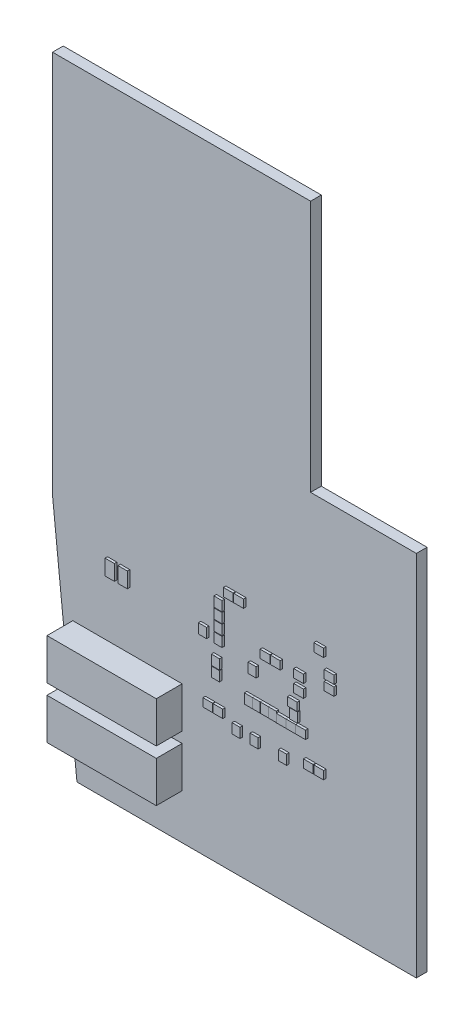
SolidWorks part; units mm, degrees
ref_plane "Front Plane" through (0, 0, 0) normal (0, 0, 1) x (1, 0, 0)
ref_plane "Top Plane" through (0, 0, 0) normal (0, 1, 0) x (1, 0, 0)
ref_plane "Right Plane" through (0, 0, 0) normal (1, 0, 0) x (0, 0, -1)
sketch "Sketch1" plane through (0, 0, 0) normal (0, 0, 1) x (1, 0, 0)
  line L0 (0, 152.4) -> (0, 57.9999)
  line L1 (0, 57.9999) -> (6, 0)
  line L2 (6, 0) -> (89.44, 0)
  line L3 (89.44, 0) -> (89.44, 90.4001)
  line L4 (89.44, 90.4001) -> (63.4401, 90.4001)
  line L5 (63.4401, 90.4001) -> (63.4401, 152.4)
  line L6 (63.4401, 152.4) -> (0, 152.4)
extrude "BOARD" add sketch "Sketch1" along normal blind 2.6289 separate body
ref_plane "Plane1" through (0, 0, 2.6289) normal (0, 0, 1) x (1, 0, 0)
sketch "Sketch2" plane through (0, 0, 0) normal (0, 0, 1) x (1, 0, 0)
  line L0 (68.9999, 30.9999) -> (40.9999, 30.9999)
  line L1 (40.9999, 30.9999) -> (40.9999, 58.9999)
  line L2 (40.9999, 58.9999) -> (68.9999, 58.9999)
  line L3 (68.9999, 58.9999) -> (68.9999, 30.9999)
extrude "PBGA_324P_1MM-1" add sketch "Sketch2" against normal blind 2.5499 separate body
sketch "R2512-1 [0]" plane through (0, 0, 0) normal (0, 0, 1) x (1, 0, 0)
  line L0 (82.9884, 66.3834) -> (82.9884, 74.5866)
  line L1 (82.9884, 74.5866) -> (87.1916, 74.5866)
  line L2 (87.1916, 74.5866) -> (87.1916, 66.3834)
  line L3 (87.1916, 66.3834) -> (82.9884, 66.3834)
sketch "C0805-1 [0]" plane through (0, 0, 0) normal (0, 0, 1) x (1, 0, 0)
  line L0 (70.9516, 70.4276) -> (70.9516, 66.2244)
  line L1 (70.9516, 66.2244) -> (68.7484, 66.2244)
  line L2 (68.7484, 66.2244) -> (68.7484, 70.4276)
  line L3 (68.7484, 70.4276) -> (70.9516, 70.4276)
sketch "Sketch5" plane through (0, 0, 0) normal (0, 0, 1) x (1, 0, 0)
  line L0 (82.3417, 64.6293) -> (75.1383, 64.6293)
  line L1 (75.1383, 64.6293) -> (75.1383, 74.8327)
  line L2 (75.1383, 74.8327) -> (82.3417, 74.8327)
  line L3 (82.3417, 74.8327) -> (82.3417, 64.6293)
extrude "SOT-223-1" add sketch "Sketch5" against normal blind 1.778 separate body
sketch "R1210-1 [0]" plane through (0, 0, 0) normal (0, 0, 1) x (1, 0, 0)
  line L0 (79.4367, 60.5785) -> (74.2333, 60.5785)
  line L1 (74.2333, 60.5785) -> (74.2333, 63.8815)
  line L2 (74.2333, 63.8815) -> (79.4367, 63.8815)
  line L3 (79.4367, 63.8815) -> (79.4367, 60.5785)
sketch "C0805-2 [0]" plane through (0, 0, 0) normal (0, 0, 1) x (1, 0, 0)
  line L0 (79.8134, 63.3316) -> (84.0166, 63.3316)
  line L1 (84.0166, 63.3316) -> (84.0166, 61.1284)
  line L2 (84.0166, 61.1284) -> (79.8134, 61.1284)
  line L3 (79.8134, 61.1284) -> (79.8134, 63.3316)
sketch "Sketch8" plane through (0, 0, 0) normal (0, 0, 1) x (1, 0, 0)
  line L0 (32.0985, 137.3518) -> (44.1018, 137.3518)
  line L1 (44.1018, 137.3518) -> (44.1018, 125.6485)
  line L2 (44.1018, 125.6485) -> (32.0985, 125.6485)
  line L3 (32.0985, 125.6485) -> (32.0985, 137.3518)
extrude "HTSSOP_32P_0_65-1" add sketch "Sketch8" against normal blind 2.65 separate body
sketch "L0805-1 [0]" plane through (0, 0, 2.6289) normal (0, 0, 1) x (1, 0, 0)
  line L0 (43.0116, 26.4734) -> (43.0116, 30.6766)
  line L1 (43.0116, 30.6766) -> (40.8084, 30.6766)
  line L2 (40.8084, 30.6766) -> (40.8084, 26.4734)
  line L3 (40.8084, 26.4734) -> (43.0116, 26.4734)
sketch "L1210-1 [0]" plane through (0, 0, 0) normal (0, 0, 1) x (1, 0, 0)
  line L0 (33.7167, 45.3385) -> (28.5133, 45.3385)
  line L1 (28.5133, 45.3385) -> (28.5133, 48.6415)
  line L2 (28.5133, 48.6415) -> (33.7167, 48.6415)
  line L3 (33.7167, 48.6415) -> (33.7167, 45.3385)
sketch "C0603-1 [0]" plane through (0, 0, 0) normal (0, 0, 1) x (1, 0, 0)
  line L0 (30.1983, 45.3017) -> (33.3017, 45.3017)
  line L1 (33.3017, 45.3017) -> (33.3017, 43.5983)
  line L2 (33.3017, 43.5983) -> (30.1983, 43.5983)
  line L3 (30.1983, 43.5983) -> (30.1983, 45.3017)
sketch "C0603-2 [0]" plane through (0, 0, 0) normal (0, 0, 1) x (1, 0, 0)
  line L0 (30.1983, 43.3967) -> (33.3017, 43.3967)
  line L1 (33.3017, 43.3967) -> (33.3017, 41.6933)
  line L2 (33.3017, 41.6933) -> (30.1983, 41.6933)
  line L3 (30.1983, 41.6933) -> (30.1983, 43.3967)
sketch "C0603-3 [0]" plane through (0, 0, 2.6289) normal (0, 0, 1) x (1, 0, 0)
  line L0 (57.4317, 60.5417) -> (54.3283, 60.5417)
  line L1 (54.3283, 60.5417) -> (54.3283, 58.8383)
  line L2 (54.3283, 58.8383) -> (57.4317, 58.8383)
  line L3 (57.4317, 58.8383) -> (57.4317, 60.5417)
sketch "R0603-1 [0]" plane through (0, 0, 2.6289) normal (0, 0, 1) x (1, 0, 0)
  line L0 (26.4483, 122.1483) -> (29.5516, 122.1483)
  line L1 (29.5516, 122.1483) -> (29.5516, 123.8517)
  line L2 (29.5516, 123.8517) -> (26.4483, 123.8517)
  line L3 (26.4483, 123.8517) -> (26.4483, 122.1483)
sketch "R0603-2 [0]" plane through (0, 0, 2.6289) normal (0, 0, 1) x (1, 0, 0)
  line L0 (34.3517, 137.9484) -> (34.3517, 141.0518)
  line L1 (34.3517, 141.0518) -> (32.6484, 141.0518)
  line L2 (32.6484, 141.0518) -> (32.6484, 137.9484)
  line L3 (32.6484, 137.9484) -> (34.3517, 137.9484)
sketch "R0603-3 [0]" plane through (0, 0, 2.6289) normal (0, 0, 1) x (1, 0, 0)
  line L0 (42.1483, 126.0516) -> (42.1483, 122.9482)
  line L1 (42.1483, 122.9482) -> (43.8516, 122.9482)
  line L2 (43.8516, 122.9482) -> (43.8516, 126.0516)
  line L3 (43.8516, 126.0516) -> (42.1483, 126.0516)
sketch "R0603-4 [0]" plane through (0, 0, 0) normal (0, 0, 1) x (1, 0, 0)
  line L0 (48.0517, 136.6484) -> (44.9483, 136.6484)
  line L1 (44.9483, 136.6484) -> (44.9483, 138.3518)
  line L2 (44.9483, 138.3518) -> (48.0517, 138.3518)
  line L3 (48.0517, 138.3518) -> (48.0517, 136.6484)
sketch "R0603-5 [0]" plane through (0, 0, 0) normal (0, 0, 1) x (1, 0, 0)
  line L0 (41.4917, 35.8417) -> (41.4917, 32.7383)
  line L1 (41.4917, 32.7383) -> (39.7883, 32.7383)
  line L2 (39.7883, 32.7383) -> (39.7883, 35.8417)
  line L3 (39.7883, 35.8417) -> (41.4917, 35.8417)
sketch "L0805-2 [0]" plane through (0, 0, 2.6289) normal (0, 0, 1) x (1, 0, 0)
  line L0 (58.2356, 62.8236) -> (54.0324, 62.8236)
  line L1 (54.0324, 62.8236) -> (54.0324, 60.6204)
  line L2 (54.0324, 60.6204) -> (58.2356, 60.6204)
  line L3 (58.2356, 60.6204) -> (58.2356, 62.8236)
sketch "R0603-6 [0]" plane through (0, 0, 2.6289) normal (0, 0, 1) x (1, 0, 0)
  line L0 (29.5516, 127.8517) -> (26.4483, 127.8517)
  line L1 (26.4483, 127.8517) -> (26.4483, 126.1483)
  line L2 (26.4483, 126.1483) -> (29.5516, 126.1483)
  line L3 (29.5516, 126.1483) -> (29.5516, 127.8517)
sketch "R0603-7 [0]" plane through (0, 0, 2.6289) normal (0, 0, 1) x (1, 0, 0)
  line L0 (29.5516, 129.8517) -> (26.4483, 129.8517)
  line L1 (26.4483, 129.8517) -> (26.4483, 128.1483)
  line L2 (26.4483, 128.1483) -> (29.5516, 128.1483)
  line L3 (29.5516, 128.1483) -> (29.5516, 129.8517)
sketch "R0603-8 [0]" plane through (0, 0, 2.6289) normal (0, 0, 1) x (1, 0, 0)
  line L0 (29.5516, 125.8517) -> (26.4483, 125.8517)
  line L1 (26.4483, 125.8517) -> (26.4483, 124.1483)
  line L2 (26.4483, 124.1483) -> (29.5516, 124.1483)
  line L3 (29.5516, 124.1483) -> (29.5516, 125.8517)
sketch "R0603-9 [0]" plane through (0, 0, 2.6289) normal (0, 0, 1) x (1, 0, 0)
  line L0 (29.5516, 131.8517) -> (26.4483, 131.8517)
  line L1 (26.4483, 131.8517) -> (26.4483, 130.1483)
  line L2 (26.4483, 130.1483) -> (29.5516, 130.1483)
  line L3 (29.5516, 130.1483) -> (29.5516, 131.8517)
sketch "R0603-10 [0]" plane through (0, 0, 2.6289) normal (0, 0, 1) x (1, 0, 0)
  line L0 (29.5516, 135.8516) -> (26.4483, 135.8516)
  line L1 (26.4483, 135.8516) -> (26.4483, 134.1483)
  line L2 (26.4483, 134.1483) -> (29.5516, 134.1483)
  line L3 (29.5516, 134.1483) -> (29.5516, 135.8516)
sketch "C0603-4 [0]" plane through (0, 0, 2.6289) normal (0, 0, 1) x (1, 0, 0)
  line L0 (43.8516, 130.4483) -> (43.8516, 133.5517)
  line L1 (43.8516, 133.5517) -> (42.1483, 133.5517)
  line L2 (42.1483, 133.5517) -> (42.1483, 130.4483)
  line L3 (42.1483, 130.4483) -> (43.8516, 130.4483)
sketch "C0603-5 [0]" plane through (0, 0, 0) normal (0, 0, 1) x (1, 0, 0)
  line L0 (52.1693, 133.3127) -> (55.2727, 133.3127)
  line L1 (55.2727, 133.3127) -> (55.2727, 131.6093)
  line L2 (55.2727, 131.6093) -> (52.1693, 131.6093)
  line L3 (52.1693, 131.6093) -> (52.1693, 133.3127)
sketch "C6032_T-1 [0]" plane through (0, 0, 0) normal (0, 0, 1) x (1, 0, 0)
  line L0 (50.8485, 117.1517) -> (61.1017, 117.1517)
  line L1 (61.1017, 117.1517) -> (61.1017, 111.8984)
  line L2 (61.1017, 111.8984) -> (50.8485, 111.8984)
  line L3 (50.8485, 111.8984) -> (50.8485, 117.1517)
sketch "C0603-6 [0]" plane through (0, 0, 0) normal (0, 0, 1) x (1, 0, 0)
  line L0 (47.3517, 131.5517) -> (47.3517, 128.4483)
  line L1 (47.3517, 128.4483) -> (45.6484, 128.4483)
  line L2 (45.6484, 128.4483) -> (45.6484, 131.5517)
  line L3 (45.6484, 131.5517) -> (47.3517, 131.5517)
sketch "C0603-7 [0]" plane through (0, 0, 0) normal (0, 0, 1) x (1, 0, 0)
  line L0 (46.4482, 126.3515) -> (49.5516, 126.3515)
  line L1 (49.5516, 126.3515) -> (49.5516, 124.6482)
  line L2 (49.5516, 124.6482) -> (46.4482, 124.6482)
  line L3 (46.4482, 124.6482) -> (46.4482, 126.3515)
sketch "SMB-1 [0]" plane through (0, 0, 0) normal (0, 0, 1) x (1, 0, 0)
  line L0 (60.6016, 101.6485) -> (52.3984, 101.6485)
  line L1 (52.3984, 101.6485) -> (52.3984, 106.3516)
  line L2 (52.3984, 106.3516) -> (60.6016, 106.3516)
  line L3 (60.6016, 106.3516) -> (60.6016, 101.6485)
sketch "C0603-8 [0]" plane through (0, 0, 0) normal (0, 0, 1) x (1, 0, 0)
  line L0 (9.6484, 128.9484) -> (9.6484, 132.0518)
  line L1 (9.6484, 132.0518) -> (11.3518, 132.0518)
  line L2 (11.3518, 132.0518) -> (11.3518, 128.9484)
  line L3 (11.3518, 128.9484) -> (9.6484, 128.9484)
sketch "R0603-11 [0]" plane through (0, 0, 2.6289) normal (0, 0, 1) x (1, 0, 0)
  line L0 (26.4483, 136.1483) -> (29.5516, 136.1483)
  line L1 (29.5516, 136.1483) -> (29.5516, 137.8516)
  line L2 (29.5516, 137.8516) -> (26.4483, 137.8516)
  line L3 (26.4483, 137.8516) -> (26.4483, 136.1483)
sketch "C0603-9 [0]" plane through (0, 0, 0) normal (0, 0, 1) x (1, 0, 0)
  line L0 (45.6484, 133.4483) -> (45.6484, 136.5517)
  line L1 (45.6484, 136.5517) -> (47.3517, 136.5517)
  line L2 (47.3517, 136.5517) -> (47.3517, 133.4483)
  line L3 (47.3517, 133.4483) -> (45.6484, 133.4483)
sketch "SMC-1 [0]" plane through (0, 0, 0) normal (0, 0, 1) x (1, 0, 0)
  line L0 (62.6326, 133.6484) -> (52.4294, 133.6484)
  line L1 (52.4294, 133.6484) -> (52.4294, 140.3515)
  line L2 (52.4294, 140.3515) -> (62.6326, 140.3515)
  line L3 (62.6326, 140.3515) -> (62.6326, 133.6484)
sketch "C0603-10 [0]" plane through (0, 0, 2.6289) normal (0, 0, 1) x (1, 0, 0)
  line L0 (34.8516, 130.4483) -> (34.8516, 133.5517)
  line L1 (34.8516, 133.5517) -> (33.1483, 133.5517)
  line L2 (33.1483, 133.5517) -> (33.1483, 130.4483)
  line L3 (33.1483, 130.4483) -> (34.8516, 130.4483)
sketch "R0603-12 [0]" plane through (0, 0, 0) normal (0, 0, 1) x (1, 0, 0)
  line L0 (29.3517, 142.0518) -> (29.3517, 138.9484)
  line L1 (29.3517, 138.9484) -> (27.6484, 138.9484)
  line L2 (27.6484, 138.9484) -> (27.6484, 142.0518)
  line L3 (27.6484, 142.0518) -> (29.3517, 142.0518)
sketch "C0603-11 [0]" plane through (0, 0, 0) normal (0, 0, 1) x (1, 0, 0)
  line L0 (25.6484, 138.9484) -> (25.6484, 142.0518)
  line L1 (25.6484, 142.0518) -> (27.3517, 142.0518)
  line L2 (27.3517, 142.0518) -> (27.3517, 138.9484)
  line L3 (27.3517, 138.9484) -> (25.6484, 138.9484)
sketch "R0603-13 [0]" plane through (0, 0, 0) normal (0, 0, 1) x (1, 0, 0)
  line L0 (33.3517, 142.0518) -> (33.3517, 138.9484)
  line L1 (33.3517, 138.9484) -> (31.6484, 138.9484)
  line L2 (31.6484, 138.9484) -> (31.6484, 142.0518)
  line L3 (31.6484, 142.0518) -> (33.3517, 142.0518)
sketch "C0603-12 [0]" plane through (0, 0, 0) normal (0, 0, 1) x (1, 0, 0)
  line L0 (31.3517, 142.0518) -> (31.3517, 138.9484)
  line L1 (31.3517, 138.9484) -> (29.6484, 138.9484)
  line L2 (29.6484, 138.9484) -> (29.6484, 142.0518)
  line L3 (29.6484, 142.0518) -> (31.3517, 142.0518)
sketch "C0603-13 [0]" plane through (0, 0, 0) normal (0, 0, 1) x (1, 0, 0)
  line L0 (35.3517, 146.5516) -> (35.3517, 143.4483)
  line L1 (35.3517, 143.4483) -> (33.6484, 143.4483)
  line L2 (33.6484, 143.4483) -> (33.6484, 146.5516)
  line L3 (33.6484, 146.5516) -> (35.3517, 146.5516)
sketch "R0603-14 [0]" plane through (0, 0, 0) normal (0, 0, 1) x (1, 0, 0)
  line L0 (34.0083, 41.4917) -> (37.1117, 41.4917)
  line L1 (37.1117, 41.4917) -> (37.1117, 39.7883)
  line L2 (37.1117, 39.7883) -> (34.0083, 39.7883)
  line L3 (34.0083, 39.7883) -> (34.0083, 41.4917)
sketch "R0603-15 [0]" plane through (0, 0, 2.6289) normal (0, 0, 1) x (1, 0, 0)
  line L0 (37.1117, 41.4917) -> (34.0083, 41.4917)
  line L1 (34.0083, 41.4917) -> (34.0083, 39.7883)
  line L2 (34.0083, 39.7883) -> (37.1117, 39.7883)
  line L3 (37.1117, 39.7883) -> (37.1117, 41.4917)
sketch "R0603-16 [0]" plane through (0, 0, 0) normal (0, 0, 1) x (1, 0, 0)
  line L0 (34.0083, 39.5867) -> (37.1117, 39.5867)
  line L1 (37.1117, 39.5867) -> (37.1117, 37.8833)
  line L2 (37.1117, 37.8833) -> (34.0083, 37.8833)
  line L3 (34.0083, 37.8833) -> (34.0083, 39.5867)
sketch "R0603-17 [0]" plane through (0, 0, 0) normal (0, 0, 1) x (1, 0, 0)
  line L0 (37.1117, 35.9783) -> (34.0083, 35.9783)
  line L1 (34.0083, 35.9783) -> (34.0083, 37.6817)
  line L2 (34.0083, 37.6817) -> (37.1117, 37.6817)
  line L3 (37.1117, 37.6817) -> (37.1117, 35.9783)
sketch "R0603-18 [0]" plane through (0, 0, 0) normal (0, 0, 1) x (1, 0, 0)
  line L0 (25.0467, 32.1683) -> (21.9433, 32.1683)
  line L1 (21.9433, 32.1683) -> (21.9433, 33.8717)
  line L2 (21.9433, 33.8717) -> (25.0467, 33.8717)
  line L3 (25.0467, 33.8717) -> (25.0467, 32.1683)
sketch "R0603-19 [0]" plane through (0, 0, 0) normal (0, 0, 1) x (1, 0, 0)
  line L0 (28.2217, 32.1683) -> (25.1183, 32.1683)
  line L1 (25.1183, 32.1683) -> (25.1183, 33.8717)
  line L2 (25.1183, 33.8717) -> (28.2217, 33.8717)
  line L3 (28.2217, 33.8717) -> (28.2217, 32.1683)
sketch "R0603-20 [0]" plane through (0, 0, 0) normal (0, 0, 1) x (1, 0, 0)
  line L0 (25.0467, 35.9783) -> (21.9433, 35.9783)
  line L1 (21.9433, 35.9783) -> (21.9433, 37.6817)
  line L2 (21.9433, 37.6817) -> (25.0467, 37.6817)
  line L3 (25.0467, 37.6817) -> (25.0467, 35.9783)
sketch "R0603-21 [0]" plane through (0, 0, 0) normal (0, 0, 1) x (1, 0, 0)
  line L0 (21.9433, 39.5867) -> (25.0467, 39.5867)
  line L1 (25.0467, 39.5867) -> (25.0467, 37.8833)
  line L2 (25.0467, 37.8833) -> (21.9433, 37.8833)
  line L3 (21.9433, 37.8833) -> (21.9433, 39.5867)
sketch "R0603-22 [0]" plane through (0, 0, 0) normal (0, 0, 1) x (1, 0, 0)
  line L0 (25.0467, 24.5483) -> (21.9433, 24.5483)
  line L1 (21.9433, 24.5483) -> (21.9433, 26.2517)
  line L2 (21.9433, 26.2517) -> (25.0467, 26.2517)
  line L3 (25.0467, 26.2517) -> (25.0467, 24.5483)
sketch "R0603-23 [0]" plane through (0, 0, 0) normal (0, 0, 1) x (1, 0, 0)
  line L0 (21.9433, 24.3467) -> (25.0467, 24.3467)
  line L1 (25.0467, 24.3467) -> (25.0467, 22.6433)
  line L2 (25.0467, 22.6433) -> (21.9433, 22.6433)
  line L3 (21.9433, 22.6433) -> (21.9433, 24.3467)
sketch "R0603-24 [0]" plane through (0, 0, 2.6289) normal (0, 0, 1) x (1, 0, 0)
  line L0 (34.7083, 29.4917) -> (34.7083, 26.3883)
  line L1 (34.7083, 26.3883) -> (36.4117, 26.3883)
  line L2 (36.4117, 26.3883) -> (36.4117, 29.4917)
  line L3 (36.4117, 29.4917) -> (34.7083, 29.4917)
sketch "R0603-25 [0]" plane through (0, 0, 2.6289) normal (0, 0, 1) x (1, 0, 0)
  line L0 (38.3167, 26.3883) -> (38.3167, 29.4917)
  line L1 (38.3167, 29.4917) -> (36.6133, 29.4917)
  line L2 (36.6133, 29.4917) -> (36.6133, 26.3883)
  line L3 (36.6133, 26.3883) -> (38.3167, 26.3883)
sketch "Sketch53" plane through (0, 0, 0) normal (0, 0, 1) x (1, 0, 0)
  line L0 (25.4935, 40.9517) -> (33.6967, 40.9517)
  line L1 (33.6967, 40.9517) -> (33.6967, 35.1485)
  line L2 (33.6967, 35.1485) -> (25.4935, 35.1485)
  line L3 (25.4935, 35.1485) -> (25.4935, 40.9517)
extrude "TSSOP_14P_0_65-1" add sketch "Sketch53" against normal blind 1.1001 separate body
sketch "Sketch54" plane through (0, 0, 0) normal (0, 0, 1) x (1, 0, 0)
  line L0 (25.4935, 30.1567) -> (33.6967, 30.1567)
  line L1 (33.6967, 30.1567) -> (33.6967, 24.3535)
  line L2 (33.6967, 24.3535) -> (25.4935, 24.3535)
  line L3 (25.4935, 24.3535) -> (25.4935, 30.1567)
extrude "TSSOP_14P_0_65-2" add sketch "Sketch54" against normal blind 1.1001 separate body
sketch "R0603-26 [0]" plane through (0, 0, 2.6289) normal (0, 0, 1) x (1, 0, 0)
  line L0 (49.3517, 122.9482) -> (49.3517, 126.0516)
  line L1 (49.3517, 126.0516) -> (47.6484, 126.0516)
  line L2 (47.6484, 126.0516) -> (47.6484, 122.9482)
  line L3 (47.6484, 122.9482) -> (49.3517, 122.9482)
sketch "R0603-27 [0]" plane through (0, 0, 2.6289) normal (0, 0, 1) x (1, 0, 0)
  line L0 (45.9483, 121.1483) -> (49.0517, 121.1483)
  line L1 (49.0517, 121.1483) -> (49.0517, 122.8517)
  line L2 (49.0517, 122.8517) -> (45.9483, 122.8517)
  line L3 (45.9483, 122.8517) -> (45.9483, 121.1483)
sketch "Sketch57" plane through (0, 0, 0) normal (0, 0, 1) x (1, 0, 0)
  line L0 (75.1502, 13.1501) -> (75.1502, 22.8498)
  line L1 (75.1502, 22.8498) -> (86.85, 22.8498)
  line L2 (86.85, 22.8498) -> (86.85, 13.1501)
  line L3 (86.85, 13.1501) -> (75.1502, 13.1501)
extrude "BGA_48P_0_8-1" add sketch "Sketch57" against normal blind 1 separate body
sketch "Sketch58" plane through (0, 0, 0) normal (0, 0, 1) x (1, 0, 0)
  line L0 (86.85, 49.8498) -> (86.85, 40.15)
  line L1 (86.85, 40.15) -> (75.1502, 40.15)
  line L2 (75.1502, 40.15) -> (75.1502, 49.8498)
  line L3 (75.1502, 49.8498) -> (86.85, 49.8498)
extrude "FBGA_48P_0_75_S-1" add sketch "Sketch58" against normal blind 1.1999 separate body
sketch "Sketch59" plane through (0, 0, 0) normal (0, 0, 1) x (1, 0, 0)
  line L0 (87.8502, 38.8501) -> (87.8502, 25.1498)
  line L1 (87.8502, 25.1498) -> (74.15, 25.1498)
  line L2 (74.15, 25.1498) -> (74.15, 38.8501)
  line L3 (74.15, 38.8501) -> (87.8502, 38.8501)
extrude "FBGA_48P_0_75-1" add sketch "Sketch59" against normal blind 1.35 separate body
sketch "Sketch60" plane through (0, 0, 0) normal (0, 0, 1) x (1, 0, 0)
  line L0 (22, 70.0001) -> (22, 84.0001)
  line L1 (22, 84.0001) -> (35.9999, 84.0001)
  line L2 (35.9999, 84.0001) -> (35.9999, 70.0001)
  line L3 (35.9999, 70.0001) -> (22, 70.0001)
extrude "TFBGA_128P_0_8-1" add sketch "Sketch60" against normal blind 1.1999 separate body
sketch "R0603-28 [0]" plane through (0, 0, 0) normal (0, 0, 1) x (1, 0, 0)
  line L0 (35.3433, 65.7583) -> (35.3433, 68.8617)
  line L1 (35.3433, 68.8617) -> (37.0467, 68.8617)
  line L2 (37.0467, 68.8617) -> (37.0467, 65.7583)
  line L3 (37.0467, 65.7583) -> (35.3433, 65.7583)
sketch "Sketch62" plane through (0, 0, 0) normal (0, 0, 1) x (1, 0, 0)
  line L0 (3.0734, 89.3582) -> (3.0734, 97.6376)
  line L1 (3.0734, 97.6376) -> (8.9167, 97.6376)
  line L2 (8.9167, 97.6376) -> (8.9167, 89.3582)
  line L3 (8.9167, 89.3582) -> (3.0734, 89.3582)
extrude "SO8-1" add sketch "Sketch62" against normal blind 1.7501 separate body
sketch "CRY_ABM11B_4P-1 [0]" plane through (0, 0, 0) normal (0, 0, 1) x (1, 0, 0)
  line L0 (31.4096, 85.4644) -> (28.3865, 85.4644)
  line L1 (28.3865, 85.4644) -> (28.3865, 87.9676)
  line L2 (28.3865, 87.9676) -> (31.4096, 87.9676)
  line L3 (31.4096, 87.9676) -> (31.4096, 85.4644)
sketch "C0603-14 [0]" plane through (0, 0, 0) normal (0, 0, 1) x (1, 0, 0)
  line L0 (29.5834, 85.4316) -> (32.6868, 85.4316)
  line L1 (32.6868, 85.4316) -> (32.6868, 83.7283)
  line L2 (32.6868, 83.7283) -> (29.5834, 83.7283)
  line L3 (29.5834, 83.7283) -> (29.5834, 85.4316)
sketch "C0603-15 [0]" plane through (0, 0, 0) normal (0, 0, 1) x (1, 0, 0)
  line L0 (29.5118, 83.7283) -> (26.4084, 83.7283)
  line L1 (26.4084, 83.7283) -> (26.4084, 85.4316)
  line L2 (26.4084, 85.4316) -> (29.5118, 85.4316)
  line L3 (29.5118, 85.4316) -> (29.5118, 83.7283)
sketch "Sketch66" plane through (0, 0, 0) normal (0, 0, 1) x (1, 0, 0)
  line L0 (32.0317, 49.4134) -> (17.0284, 49.4134)
  line L1 (17.0284, 49.4134) -> (17.0284, 63.6166)
  line L2 (17.0284, 63.6166) -> (32.0317, 63.6166)
  line L3 (32.0317, 63.6166) -> (32.0317, 49.4134)
extrude "TQFP_44P_0_8-1" add sketch "Sketch66" against normal blind 1.1999 separate body
sketch "R0603-29 [0]" plane through (0, 0, 0) normal (0, 0, 1) x (1, 0, 0)
  line L0 (53.7583, 65.7583) -> (53.7583, 68.8617)
  line L1 (53.7583, 68.8617) -> (55.4617, 68.8617)
  line L2 (55.4617, 68.8617) -> (55.4617, 65.7583)
  line L3 (55.4617, 65.7583) -> (53.7583, 65.7583)
sketch "Sketch68" plane through (0, 0, 0) normal (0, 0, 1) x (1, 0, 0)
  line L0 (59.7916, 98.6018) -> (59.7916, 90.3224)
  line L1 (59.7916, 90.3224) -> (53.9483, 90.3224)
  line L2 (53.9483, 90.3224) -> (53.9483, 98.6018)
  line L3 (53.9483, 98.6018) -> (59.7916, 98.6018)
extrude "SO8-2" add sketch "Sketch68" against normal blind 1.7501 separate body
sketch "CRY_ABM11B_4P-2 [0]" plane through (0, 0, 0) normal (0, 0, 1) x (1, 0, 0)
  line L0 (52.5856, 84.7644) -> (49.5625, 84.7644)
  line L1 (49.5625, 84.7644) -> (49.5625, 87.2675)
  line L2 (49.5625, 87.2675) -> (52.5856, 87.2675)
  line L3 (52.5856, 87.2675) -> (52.5856, 84.7644)
sketch "R0603-30 [0]" plane through (0, 0, 2.6289) normal (0, 0, 1) x (1, 0, 0)
  line L0 (41.6283, 79.1583) -> (44.7317, 79.1583)
  line L1 (44.7317, 79.1583) -> (44.7317, 80.8617)
  line L2 (44.7317, 80.8617) -> (41.6283, 80.8617)
  line L3 (41.6283, 80.8617) -> (41.6283, 79.1583)
sketch "C0603-16 [0]" plane through (0, 0, 0) normal (0, 0, 1) x (1, 0, 0)
  line L0 (50.7723, 84.9257) -> (53.8757, 84.9257)
  line L1 (53.8757, 84.9257) -> (53.8757, 83.2223)
  line L2 (53.8757, 83.2223) -> (50.7723, 83.2223)
  line L3 (50.7723, 83.2223) -> (50.7723, 84.9257)
sketch "C0603-17 [0]" plane through (0, 0, 0) normal (0, 0, 1) x (1, 0, 0)
  line L0 (50.8277, 83.2223) -> (47.7243, 83.2223)
  line L1 (47.7243, 83.2223) -> (47.7243, 84.9257)
  line L2 (47.7243, 84.9257) -> (50.8277, 84.9257)
  line L3 (50.8277, 84.9257) -> (50.8277, 83.2223)
sketch "C0805-3 [0]" plane through (0, 0, 2.6289) normal (0, 0, 1) x (1, 0, 0)
  line L0 (56.3184, 66.2084) -> (60.5216, 66.2084)
  line L1 (60.5216, 66.2084) -> (60.5216, 68.4116)
  line L2 (60.5216, 68.4116) -> (56.3184, 68.4116)
  line L3 (56.3184, 68.4116) -> (56.3184, 66.2084)
sketch "C0805-4 [0]" plane through (0, 0, 2.6289) normal (0, 0, 1) x (1, 0, 0)
  line L0 (4.8834, 95.4184) -> (9.0866, 95.4184)
  line L1 (9.0866, 95.4184) -> (9.0866, 97.6216)
  line L2 (9.0866, 97.6216) -> (4.8834, 97.6216)
  line L3 (4.8834, 97.6216) -> (4.8834, 95.4184)
sketch "C0805-5 [0]" plane through (0, 0, 2.6289) normal (0, 0, 1) x (1, 0, 0)
  line L0 (24.5966, 84.2584) -> (24.5966, 88.4616)
  line L1 (24.5966, 88.4616) -> (22.3934, 88.4616)
  line L2 (22.3934, 88.4616) -> (22.3934, 84.2584)
  line L3 (22.3934, 84.2584) -> (24.5966, 84.2584)
sketch "C0805-6 [0]" plane through (0, 0, 2.6289) normal (0, 0, 1) x (1, 0, 0)
  line L0 (21.7866, 88.0966) -> (17.5834, 88.0966)
  line L1 (17.5834, 88.0966) -> (17.5834, 85.8934)
  line L2 (17.5834, 85.8934) -> (21.7866, 85.8934)
  line L3 (21.7866, 85.8934) -> (21.7866, 88.0966)
sketch "C0805-7 [0]" plane through (0, 0, 2.6289) normal (0, 0, 1) x (1, 0, 0)
  line L0 (40.8084, 67.5066) -> (40.8084, 63.3034)
  line L1 (40.8084, 63.3034) -> (43.0116, 63.3034)
  line L2 (43.0116, 63.3034) -> (43.0116, 67.5066)
  line L3 (43.0116, 67.5066) -> (40.8084, 67.5066)
sketch "R0603-31 [0]" plane through (0, 0, 2.6289) normal (0, 0, 1) x (1, 0, 0)
  line L0 (41.6283, 77.2533) -> (44.7317, 77.2533)
  line L1 (44.7317, 77.2533) -> (44.7317, 78.9567)
  line L2 (44.7317, 78.9567) -> (41.6283, 78.9567)
  line L3 (41.6283, 78.9567) -> (41.6283, 77.2533)
sketch "Sketch79" plane through (0, 0, 0) normal (0, 0, 1) x (1, 0, 0)
  line L0 (43.9999, 70.0001) -> (43.9999, 84.0001)
  line L1 (43.9999, 84.0001) -> (57.9999, 84.0001)
  line L2 (57.9999, 84.0001) -> (57.9999, 70.0001)
  line L3 (57.9999, 70.0001) -> (43.9999, 70.0001)
extrude "TFBGA_128P_0_8-2" add sketch "Sketch79" against normal blind 1.1999 separate body
sketch "C0805-8 [0]" plane through (0, 0, 2.6289) normal (0, 0, 1) x (1, 0, 0)
  line L0 (57.9816, 92.5416) -> (53.7784, 92.5416)
  line L1 (53.7784, 92.5416) -> (53.7784, 90.3384)
  line L2 (53.7784, 90.3384) -> (57.9816, 90.3384)
  line L3 (57.9816, 90.3384) -> (57.9816, 92.5416)
sketch "C0603-18 [0]" plane through (0, 0, 2.6289) normal (0, 0, 1) x (1, 0, 0)
  line L0 (26.3167, 63.0817) -> (23.2133, 63.0817)
  line L1 (23.2133, 63.0817) -> (23.2133, 61.3783)
  line L2 (23.2133, 61.3783) -> (26.3167, 61.3783)
  line L3 (26.3167, 61.3783) -> (26.3167, 63.0817)
sketch "C0603-19 [0]" plane through (0, 0, 2.6289) normal (0, 0, 1) x (1, 0, 0)
  line L0 (23.2133, 49.9483) -> (26.3167, 49.9483)
  line L1 (26.3167, 49.9483) -> (26.3167, 51.6517)
  line L2 (26.3167, 51.6517) -> (23.2133, 51.6517)
  line L3 (23.2133, 51.6517) -> (23.2133, 49.9483)
sketch "C0603-20 [0]" plane through (0, 0, 2.6289) normal (0, 0, 1) x (1, 0, 0)
  line L0 (26.3167, 64.9867) -> (23.2133, 64.9867)
  line L1 (23.2133, 64.9867) -> (23.2133, 63.2833)
  line L2 (23.2133, 63.2833) -> (26.3167, 63.2833)
  line L3 (26.3167, 63.2833) -> (26.3167, 64.9867)
sketch "C0603-21 [0]" plane through (0, 0, 2.6289) normal (0, 0, 1) x (1, 0, 0)
  line L0 (19.2667, 56.4873) -> (19.2667, 59.5907)
  line L1 (19.2667, 59.5907) -> (17.5633, 59.5907)
  line L2 (17.5633, 59.5907) -> (17.5633, 56.4873)
  line L3 (17.5633, 56.4873) -> (19.2667, 56.4873)
sketch "C3216_T-1 [0]" plane through (0, 0, 0) normal (0, 0, 1) x (1, 0, 0)
  line L0 (19.6235, 71.4157) -> (19.6235, 64.4624)
  line L1 (19.6235, 64.4624) -> (15.6703, 64.4624)
  line L2 (15.6703, 64.4624) -> (15.6703, 71.4157)
  line L3 (15.6703, 71.4157) -> (19.6235, 71.4157)
sketch "R0603-32 [0]" plane through (0, 0, 2.6289) normal (0, 0, 1) x (1, 0, 0)
  line L0 (6.7683, 57.4317) -> (6.7683, 54.3283)
  line L1 (6.7683, 54.3283) -> (8.4717, 54.3283)
  line L2 (8.4717, 54.3283) -> (8.4717, 57.4317)
  line L3 (8.4717, 57.4317) -> (6.7683, 57.4317)
sketch "R0603-33 [0]" plane through (0, 0, 2.6289) normal (0, 0, 1) x (1, 0, 0)
  line L0 (8.4717, 58.1383) -> (8.4717, 61.2417)
  line L1 (8.4717, 61.2417) -> (6.7683, 61.2417)
  line L2 (6.7683, 61.2417) -> (6.7683, 58.1383)
  line L3 (6.7683, 58.1383) -> (8.4717, 58.1383)
sketch "R0603-34 [0]" plane through (0, 0, 2.6289) normal (0, 0, 1) x (1, 0, 0)
  line L0 (6.7683, 65.0517) -> (6.7683, 61.9483)
  line L1 (6.7683, 61.9483) -> (8.4717, 61.9483)
  line L2 (8.4717, 61.9483) -> (8.4717, 65.0517)
  line L3 (8.4717, 65.0517) -> (6.7683, 65.0517)
sketch "R0603-35 [0]" plane through (0, 0, 2.6289) normal (0, 0, 1) x (1, 0, 0)
  line L0 (12.9817, 52.2867) -> (9.8783, 52.2867)
  line L1 (9.8783, 52.2867) -> (9.8783, 50.5833)
  line L2 (9.8783, 50.5833) -> (12.9817, 50.5833)
  line L3 (12.9817, 50.5833) -> (12.9817, 52.2867)
sketch "R0603-36 [0]" plane through (0, 0, 0) normal (0, 0, 1) x (1, 0, 0)
  line L0 (18.7683, 81.4967) -> (21.8717, 81.4967)
  line L1 (21.8717, 81.4967) -> (21.8717, 79.7933)
  line L2 (21.8717, 79.7933) -> (18.7683, 79.7933)
  line L3 (18.7683, 79.7933) -> (18.7683, 81.4967)
sketch "R0603-37 [0]" plane through (0, 0, 0) normal (0, 0, 1) x (1, 0, 0)
  line L0 (18.7683, 79.5917) -> (21.8717, 79.5917)
  line L1 (21.8717, 79.5917) -> (21.8717, 77.8883)
  line L2 (21.8717, 77.8883) -> (18.7683, 77.8883)
  line L3 (18.7683, 77.8883) -> (18.7683, 79.5917)
sketch "C0603-22 [0]" plane through (0, 0, 0) normal (0, 0, 1) x (1, 0, 0)
  line L0 (29.5633, 16.0917) -> (32.6667, 16.0917)
  line L1 (32.6667, 16.0917) -> (32.6667, 14.3883)
  line L2 (32.6667, 14.3883) -> (29.5633, 14.3883)
  line L3 (29.5633, 14.3883) -> (29.5633, 16.0917)
sketch "C0603-23 [0]" plane through (0, 0, 0) normal (0, 0, 1) x (1, 0, 0)
  line L0 (26.8867, 23.1417) -> (26.8867, 20.0383)
  line L1 (26.8867, 20.0383) -> (25.1833, 20.0383)
  line L2 (25.1833, 20.0383) -> (25.1833, 23.1417)
  line L3 (25.1833, 23.1417) -> (26.8867, 23.1417)
sketch "C3528_T-1 [0]" plane through (0, 0, 0) normal (0, 0, 1) x (1, 0, 0)
  line L0 (40.6984, 106.6483) -> (40.6984, 113.6015)
  line L1 (40.6984, 113.6015) -> (45.6016, 113.6015)
  line L2 (45.6016, 113.6015) -> (45.6016, 106.6483)
  line L3 (45.6016, 106.6483) -> (40.6984, 106.6483)
sketch "C3528_T-2 [0]" plane through (0, 0, 0) normal (0, 0, 1) x (1, 0, 0)
  line L0 (37.3517, 100.1984) -> (30.3985, 100.1984)
  line L1 (30.3985, 100.1984) -> (30.3985, 105.1016)
  line L2 (30.3985, 105.1016) -> (37.3517, 105.1016)
  line L3 (37.3517, 105.1016) -> (37.3517, 100.1984)
sketch "C3528_T-3 [0]" plane through (0, 0, 0) normal (0, 0, 1) x (1, 0, 0)
  line L0 (45.6984, 106.6483) -> (45.6984, 113.6015)
  line L1 (45.6984, 113.6015) -> (50.6016, 113.6015)
  line L2 (50.6016, 113.6015) -> (50.6016, 106.6483)
  line L3 (50.6016, 106.6483) -> (45.6984, 106.6483)
sketch "C0603-24 [0]" plane through (0, 0, 0) normal (0, 0, 1) x (1, 0, 0)
  line L0 (31.9484, 113.3516) -> (35.0517, 113.3516)
  line L1 (35.0517, 113.3516) -> (35.0517, 111.6482)
  line L2 (35.0517, 111.6482) -> (31.9484, 111.6482)
  line L3 (31.9484, 111.6482) -> (31.9484, 113.3516)
sketch "R0805-1 [0]" plane through (0, 0, 0) normal (0, 0, 1) x (1, 0, 0)
  line L0 (42.6016, 101.8984) -> (38.3984, 101.8984)
  line L1 (38.3984, 101.8984) -> (38.3984, 104.1016)
  line L2 (38.3984, 104.1016) -> (42.6016, 104.1016)
  line L3 (42.6016, 104.1016) -> (42.6016, 101.8984)
sketch "R0805-2 [0]" plane through (0, 0, 0) normal (0, 0, 1) x (1, 0, 0)
  line L0 (38.3984, 104.3983) -> (38.3984, 108.6015)
  line L1 (38.3984, 108.6015) -> (40.6016, 108.6015)
  line L2 (40.6016, 108.6015) -> (40.6016, 104.3983)
  line L3 (40.6016, 104.3983) -> (38.3984, 104.3983)
sketch "C0603-25 [0]" plane through (0, 0, 0) normal (0, 0, 1) x (1, 0, 0)
  line L0 (38.6484, 108.9482) -> (38.6484, 112.0516)
  line L1 (38.6484, 112.0516) -> (40.3517, 112.0516)
  line L2 (40.3517, 112.0516) -> (40.3517, 108.9482)
  line L3 (40.3517, 108.9482) -> (38.6484, 108.9482)
sketch "SMA-1 [0]" plane through (0, 0, 0) normal (0, 0, 1) x (1, 0, 0)
  line L0 (24.1483, 106.6483) -> (24.1483, 114.3516)
  line L1 (24.1483, 114.3516) -> (27.8516, 114.3516)
  line L2 (27.8516, 114.3516) -> (27.8516, 106.6483)
  line L3 (27.8516, 106.6483) -> (24.1483, 106.6483)
sketch "R0805-3 [0]" plane through (0, 0, 0) normal (0, 0, 1) x (1, 0, 0)
  line L0 (5.3985, 103.8984) -> (5.3985, 108.1016)
  line L1 (5.3985, 108.1016) -> (7.6017, 108.1016)
  line L2 (7.6017, 108.1016) -> (7.6017, 103.8984)
  line L3 (7.6017, 103.8984) -> (5.3985, 103.8984)
sketch "C3528_T-4 [0]" plane through (0, 0, 0) normal (0, 0, 1) x (1, 0, 0)
  line L0 (24.3017, 106.8517) -> (24.3017, 99.8985)
  line L1 (24.3017, 99.8985) -> (19.3985, 99.8985)
  line L2 (19.3985, 99.8985) -> (19.3985, 106.8517)
  line L3 (19.3985, 106.8517) -> (24.3017, 106.8517)
sketch "C3528_T-5 [0]" plane through (0, 0, 0) normal (0, 0, 1) x (1, 0, 0)
  line L0 (28.8016, 106.8517) -> (28.8016, 99.8985)
  line L1 (28.8016, 99.8985) -> (23.8984, 99.8985)
  line L2 (23.8984, 99.8985) -> (23.8984, 106.8517)
  line L3 (23.8984, 106.8517) -> (28.8016, 106.8517)
sketch "C3528_T-6 [0]" plane through (0, 0, 0) normal (0, 0, 1) x (1, 0, 0)
  line L0 (9.6985, 107.6482) -> (9.6985, 114.6015)
  line L1 (9.6985, 114.6015) -> (14.6017, 114.6015)
  line L2 (14.6017, 114.6015) -> (14.6017, 107.6482)
  line L3 (14.6017, 107.6482) -> (9.6985, 107.6482)
sketch "Sketch106" plane through (0, 0, 0) normal (0, 0, 1) x (1, 0, 0)
  line L0 (38.1218, 105.8583) -> (29.8425, 105.8583)
  line L1 (29.8425, 105.8583) -> (29.8425, 111.7016)
  line L2 (29.8425, 111.7016) -> (38.1218, 111.7016)
  line L3 (38.1218, 111.7016) -> (38.1218, 105.8583)
extrude "SO8-3" add sketch "Sketch106" against normal blind 1.7501 separate body
sketch "R0805-4 [0]" plane through (0, 0, 0) normal (0, 0, 1) x (1, 0, 0)
  line L0 (9.6017, 101.3983) -> (5.3985, 101.3983)
  line L1 (5.3985, 101.3983) -> (5.3985, 103.6015)
  line L2 (5.3985, 103.6015) -> (9.6017, 103.6015)
  line L3 (9.6017, 103.6015) -> (9.6017, 101.3983)
sketch "R0805-5 [0]" plane through (0, 0, 0) normal (0, 0, 1) x (1, 0, 0)
  line L0 (19.1016, 105.1016) -> (19.1016, 100.8985)
  line L1 (19.1016, 100.8985) -> (16.8984, 100.8985)
  line L2 (16.8984, 100.8985) -> (16.8984, 105.1016)
  line L3 (16.8984, 105.1016) -> (19.1016, 105.1016)
sketch "C3528_T-7 [0]" plane through (0, 0, 0) normal (0, 0, 1) x (1, 0, 0)
  line L0 (4.6985, 107.6482) -> (4.6985, 114.6015)
  line L1 (4.6985, 114.6015) -> (9.6017, 114.6015)
  line L2 (9.6017, 114.6015) -> (9.6017, 107.6482)
  line L3 (9.6017, 107.6482) -> (4.6985, 107.6482)
sketch "C0603-26 [0]" plane through (0, 0, 2.6289) normal (0, 0, 1) x (1, 0, 0)
  line L0 (7.1483, 138.5517) -> (7.1483, 135.4483)
  line L1 (7.1483, 135.4483) -> (8.8516, 135.4483)
  line L2 (8.8516, 135.4483) -> (8.8516, 138.5517)
  line L3 (8.8516, 138.5517) -> (7.1483, 138.5517)
sketch "R0603-38 [0]" plane through (0, 0, 2.6289) normal (0, 0, 1) x (1, 0, 0)
  line L0 (31.5333, 40.9217) -> (31.5333, 37.8183)
  line L1 (31.5333, 37.8183) -> (33.2367, 37.8183)
  line L2 (33.2367, 37.8183) -> (33.2367, 40.9217)
  line L3 (33.2367, 40.9217) -> (31.5333, 40.9217)
sketch "R0603-39 [0]" plane through (0, 0, 0) normal (0, 0, 1) x (1, 0, 0)
  line L0 (25.0467, 39.7883) -> (21.9433, 39.7883)
  line L1 (21.9433, 39.7883) -> (21.9433, 41.4917)
  line L2 (21.9433, 41.4917) -> (25.0467, 41.4917)
  line L3 (25.0467, 41.4917) -> (25.0467, 39.7883)
sketch "R0603-40 [0]" plane through (0, 0, 0) normal (0, 0, 1) x (1, 0, 0)
  line L0 (25.0467, 26.4533) -> (21.9433, 26.4533)
  line L1 (21.9433, 26.4533) -> (21.9433, 28.1567)
  line L2 (21.9433, 28.1567) -> (25.0467, 28.1567)
  line L3 (25.0467, 28.1567) -> (25.0467, 26.4533)
sketch "R0603-41 [0]" plane through (0, 0, 0) normal (0, 0, 1) x (1, 0, 0)
  line L0 (31.5333, 30.8333) -> (31.5333, 33.9367)
  line L1 (31.5333, 33.9367) -> (33.2367, 33.9367)
  line L2 (33.2367, 33.9367) -> (33.2367, 30.8333)
  line L3 (33.2367, 30.8333) -> (31.5333, 30.8333)
sketch "R0603-42 [0]" plane through (0, 0, 2.6289) normal (0, 0, 1) x (1, 0, 0)
  line L0 (25.8183, 38.3817) -> (25.8183, 35.2783)
  line L1 (25.8183, 35.2783) -> (27.5217, 35.2783)
  line L2 (27.5217, 35.2783) -> (27.5217, 38.3817)
  line L3 (27.5217, 38.3817) -> (25.8183, 38.3817)
sketch "C0603-27 [0]" plane through (0, 0, 0) normal (0, 0, 1) x (1, 0, 0)
  line L0 (9.3518, 107.5517) -> (9.3518, 104.4484)
  line L1 (9.3518, 104.4484) -> (7.6484, 104.4484)
  line L2 (7.6484, 104.4484) -> (7.6484, 107.5517)
  line L3 (7.6484, 107.5517) -> (9.3518, 107.5517)
sketch "R0603-43 [0]" plane through (0, 0, 0) normal (0, 0, 1) x (1, 0, 0)
  line L0 (29.6283, 30.8333) -> (29.6283, 33.9367)
  line L1 (29.6283, 33.9367) -> (31.3317, 33.9367)
  line L2 (31.3317, 33.9367) -> (31.3317, 30.8333)
  line L3 (31.3317, 30.8333) -> (29.6283, 30.8333)
sketch "R0603-44 [0]" plane through (0, 0, 2.6289) normal (0, 0, 1) x (1, 0, 0)
  line L0 (29.4267, 35.2783) -> (29.4267, 38.3817)
  line L1 (29.4267, 38.3817) -> (27.7233, 38.3817)
  line L2 (27.7233, 38.3817) -> (27.7233, 35.2783)
  line L3 (27.7233, 35.2783) -> (29.4267, 35.2783)
sketch "CRY_4P_ASDMB-1 [0]" plane through (0, 0, 0) normal (0, 0, 1) x (1, 0, 0)
  line L0 (36.2255, 45.0357) -> (39.8287, 45.0357)
  line L1 (39.8287, 45.0357) -> (39.8287, 41.8323)
  line L2 (39.8287, 41.8323) -> (36.2255, 41.8323)
  line L3 (36.2255, 41.8323) -> (36.2255, 45.0357)
sketch "R0603-45 [0]" plane through (0, 0, 0) normal (0, 0, 1) x (1, 0, 0)
  line L0 (30.6967, 23.1417) -> (30.6967, 20.0383)
  line L1 (30.6967, 20.0383) -> (28.9933, 20.0383)
  line L2 (28.9933, 20.0383) -> (28.9933, 23.1417)
  line L3 (28.9933, 23.1417) -> (30.6967, 23.1417)
sketch "R0603-46 [0]" plane through (0, 0, 0) normal (0, 0, 1) x (1, 0, 0)
  line L0 (29.5633, 17.9967) -> (32.6667, 17.9967)
  line L1 (32.6667, 17.9967) -> (32.6667, 16.2933)
  line L2 (32.6667, 16.2933) -> (29.5633, 16.2933)
  line L3 (29.5633, 16.2933) -> (29.5633, 17.9967)
sketch "R0603-47 [0]" plane through (0, 0, 0) normal (0, 0, 1) x (1, 0, 0)
  line L0 (25.0467, 34.0733) -> (21.9433, 34.0733)
  line L1 (21.9433, 34.0733) -> (21.9433, 35.7767)
  line L2 (21.9433, 35.7767) -> (25.0467, 35.7767)
  line L3 (25.0467, 35.7767) -> (25.0467, 34.0733)
sketch "C0603-28 [0]" plane through (0, 0, 0) normal (0, 0, 1) x (1, 0, 0)
  line L0 (23.6484, 144.9484) -> (23.6484, 148.0518)
  line L1 (23.6484, 148.0518) -> (25.3517, 148.0518)
  line L2 (25.3517, 148.0518) -> (25.3517, 144.9484)
  line L3 (25.3517, 144.9484) -> (23.6484, 144.9484)
sketch "C0603-29 [0]" plane through (0, 0, 0) normal (0, 0, 1) x (1, 0, 0)
  line L0 (21.8516, 124.0516) -> (21.8516, 120.9482)
  line L1 (21.8516, 120.9482) -> (20.1483, 120.9482)
  line L2 (20.1483, 120.9482) -> (20.1483, 124.0516)
  line L3 (20.1483, 124.0516) -> (21.8516, 124.0516)
sketch "C0603-30 [0]" plane through (0, 0, 0) normal (0, 0, 1) x (1, 0, 0)
  line L0 (29.6484, 131.9484) -> (29.6484, 135.0518)
  line L1 (29.6484, 135.0518) -> (31.3517, 135.0518)
  line L2 (31.3517, 135.0518) -> (31.3517, 131.9484)
  line L3 (31.3517, 131.9484) -> (29.6484, 131.9484)
sketch "C3216_T-2 [0]" plane through (0, 0, 0) normal (0, 0, 1) x (1, 0, 0)
  line L0 (25.1485, 129.6485) -> (25.1485, 136.6017)
  line L1 (25.1485, 136.6017) -> (29.1018, 136.6017)
  line L2 (29.1018, 136.6017) -> (29.1018, 129.6485)
  line L3 (29.1018, 129.6485) -> (25.1485, 129.6485)
sketch "L0805-3 [0]" plane through (0, 0, 0) normal (0, 0, 1) x (1, 0, 0)
  line L0 (24.1016, 116.3983) -> (19.8984, 116.3983)
  line L1 (19.8984, 116.3983) -> (19.8984, 118.6015)
  line L2 (19.8984, 118.6015) -> (24.1016, 118.6015)
  line L3 (24.1016, 118.6015) -> (24.1016, 116.3983)
sketch "L0805-4 [0]" plane through (0, 0, 0) normal (0, 0, 1) x (1, 0, 0)
  line L0 (11.3985, 120.8984) -> (11.3985, 125.1016)
  line L1 (11.3985, 125.1016) -> (13.6017, 125.1016)
  line L2 (13.6017, 125.1016) -> (13.6017, 120.8984)
  line L3 (13.6017, 120.8984) -> (11.3985, 120.8984)
sketch "C3216_T-3 [0]" plane through (0, 0, 0) normal (0, 0, 1) x (1, 0, 0)
  line L0 (11.8516, 122.8517) -> (11.8516, 115.8984)
  line L1 (11.8516, 115.8984) -> (7.8984, 115.8984)
  line L2 (7.8984, 115.8984) -> (7.8984, 122.8517)
  line L3 (7.8984, 122.8517) -> (11.8516, 122.8517)
sketch "L0805-5 [0]" plane through (0, 0, 0) normal (0, 0, 1) x (1, 0, 0)
  line L0 (6.8984, 125.1016) -> (11.1016, 125.1016)
  line L1 (11.1016, 125.1016) -> (11.1016, 122.8984)
  line L2 (11.1016, 122.8984) -> (6.8984, 122.8984)
  line L3 (6.8984, 122.8984) -> (6.8984, 125.1016)
sketch "C3216_T-4 [0]" plane through (0, 0, 0) normal (0, 0, 1) x (1, 0, 0)
  line L0 (8.3515, 122.8517) -> (8.3515, 115.8984)
  line L1 (8.3515, 115.8984) -> (4.3983, 115.8984)
  line L2 (4.3983, 115.8984) -> (4.3983, 122.8517)
  line L3 (4.3983, 122.8517) -> (8.3515, 122.8517)
sketch "R1210-2 [0]" plane through (0, 0, 0) normal (0, 0, 1) x (1, 0, 0)
  line L0 (68.3265, 72.8327) -> (68.3265, 67.6293)
  line L1 (68.3265, 67.6293) -> (65.0235, 67.6293)
  line L2 (65.0235, 67.6293) -> (65.0235, 72.8327)
  line L3 (65.0235, 72.8327) -> (68.3265, 72.8327)
sketch "R1210-3 [0]" plane through (0, 0, 0) normal (0, 0, 1) x (1, 0, 0)
  line L0 (71.3735, 65.7243) -> (71.3735, 70.9277)
  line L1 (71.3735, 70.9277) -> (74.6765, 70.9277)
  line L2 (74.6765, 70.9277) -> (74.6765, 65.7243)
  line L3 (74.6765, 65.7243) -> (71.3735, 65.7243)
sketch "C0805-9 [0]" plane through (0, 0, 0) normal (0, 0, 1) x (1, 0, 0)
  line L0 (64.5734, 66.8876) -> (68.7766, 66.8876)
  line L1 (68.7766, 66.8876) -> (68.7766, 64.6844)
  line L2 (68.7766, 64.6844) -> (64.5734, 64.6844)
  line L3 (64.5734, 64.6844) -> (64.5734, 66.8876)
sketch "C0805-10 [0]" plane through (0, 0, 0) normal (0, 0, 1) x (1, 0, 0)
  line L0 (14.1016, 108.1016) -> (14.1016, 103.8984)
  line L1 (14.1016, 103.8984) -> (11.8984, 103.8984)
  line L2 (11.8984, 103.8984) -> (11.8984, 108.1016)
  line L3 (11.8984, 108.1016) -> (14.1016, 108.1016)
sketch "C0603-31 [0]" plane through (0, 0, 0) normal (0, 0, 1) x (1, 0, 0)
  line L0 (62.5117, 58.8383) -> (59.4083, 58.8383)
  line L1 (59.4083, 58.8383) -> (59.4083, 60.5417)
  line L2 (59.4083, 60.5417) -> (62.5117, 60.5417)
  line L3 (62.5117, 60.5417) -> (62.5117, 58.8383)
sketch "R0603-48 [0]" plane through (0, 0, 0) normal (0, 0, 1) x (1, 0, 0)
  line L0 (62.5117, 60.7433) -> (59.4083, 60.7433)
  line L1 (59.4083, 60.7433) -> (59.4083, 62.4467)
  line L2 (59.4083, 62.4467) -> (62.5117, 62.4467)
  line L3 (62.5117, 62.4467) -> (62.5117, 60.7433)
sketch "C0603-32 [0]" plane through (0, 0, 2.6289) normal (0, 0, 1) x (1, 0, 0)
  line L0 (28.9933, 54.8917) -> (28.9933, 51.7883)
  line L1 (28.9933, 51.7883) -> (30.6967, 51.7883)
  line L2 (30.6967, 51.7883) -> (30.6967, 54.8917)
  line L3 (30.6967, 54.8917) -> (28.9933, 54.8917)
sketch "C0805-11 [0]" plane through (0, 0, 0) normal (0, 0, 1) x (1, 0, 0)
  line L0 (50.1015, 131.6017) -> (50.1015, 127.3985)
  line L1 (50.1015, 127.3985) -> (47.8983, 127.3985)
  line L2 (47.8983, 127.3985) -> (47.8983, 131.6017)
  line L3 (47.8983, 131.6017) -> (50.1015, 131.6017)
sketch "Sketch140" plane through (0, 0, 0) normal (0, 0, 1) x (1, 0, 0)
  line L0 (32.1328, 48.5717) -> (32.1328, 57.5419)
  line L1 (32.1328, 57.5419) -> (35.987, 57.5419)
  line L2 (35.987, 57.5419) -> (35.987, 48.5717)
  line L3 (35.987, 48.5717) -> (32.1328, 48.5717)
extrude "TSSOP_8P_0_65-1" add sketch "Sketch140" against normal blind 1.1999 separate body
sketch "R0805-6 [0]" plane through (0, 0, 0) normal (0, 0, 1) x (1, 0, 0)
  line L0 (37.9034, 38.5666) -> (42.1066, 38.5666)
  line L1 (42.1066, 38.5666) -> (42.1066, 36.3634)
  line L2 (42.1066, 36.3634) -> (37.9034, 36.3634)
  line L3 (37.9034, 36.3634) -> (37.9034, 38.5666)
sketch "R0603-49 [0]" plane through (0, 0, 2.6289) normal (0, 0, 1) x (1, 0, 0)
  line L0 (81.4967, 78.4583) -> (81.4967, 81.5617)
  line L1 (81.4967, 81.5617) -> (79.7933, 81.5617)
  line L2 (79.7933, 81.5617) -> (79.7933, 78.4583)
  line L3 (79.7933, 78.4583) -> (81.4967, 78.4583)
sketch "R0603-50 [0]" plane through (0, 0, 2.6289) normal (0, 0, 1) x (1, 0, 0)
  line L0 (77.8883, 81.5617) -> (77.8883, 78.4583)
  line L1 (77.8883, 78.4583) -> (79.5917, 78.4583)
  line L2 (79.5917, 78.4583) -> (79.5917, 81.5617)
  line L3 (79.5917, 81.5617) -> (77.8883, 81.5617)
sketch "R0603-51 [0]" plane through (0, 0, 2.6289) normal (0, 0, 1) x (1, 0, 0)
  line L0 (84.1116, 83.8032) -> (84.1116, 86.9066)
  line L1 (84.1116, 86.9066) -> (82.4083, 86.9066)
  line L2 (82.4083, 86.9066) -> (82.4083, 83.8032)
  line L3 (82.4083, 83.8032) -> (84.1116, 83.8032)
sketch "R0603-52 [0]" plane through (0, 0, 2.6289) normal (0, 0, 1) x (1, 0, 0)
  line L0 (84.4083, 86.9066) -> (84.4083, 83.8032)
  line L1 (84.4083, 83.8032) -> (86.1116, 83.8032)
  line L2 (86.1116, 83.8032) -> (86.1116, 86.9066)
  line L3 (86.1116, 86.9066) -> (84.4083, 86.9066)
sketch "MH_3_55MM-1 [0]" plane through (0, 0, 2.6289) normal (0, 0, 1) x (1, 0, 0)
  line L0 (2.5029, 143.4028) -> (8.4973, 143.4028)
  line L1 (8.4973, 143.4028) -> (8.4973, 149.3972)
  line L2 (8.4973, 149.3972) -> (2.5029, 149.3972)
  line L3 (2.5029, 149.3972) -> (2.5029, 143.4028)
sketch "MH_3_55MM-2 [0]" plane through (0, 0, 2.6289) normal (0, 0, 1) x (1, 0, 0)
  line L0 (7.0028, 3.0028) -> (12.9972, 3.0028)
  line L1 (12.9972, 3.0028) -> (12.9972, 8.9972)
  line L2 (12.9972, 8.9972) -> (7.0028, 8.9972)
  line L3 (7.0028, 8.9972) -> (7.0028, 3.0028)
sketch "MH_3_55MM-3 [0]" plane through (0, 0, 2.6289) normal (0, 0, 1) x (1, 0, 0)
  line L0 (76.4428, 3.0028) -> (82.4372, 3.0028)
  line L1 (82.4372, 3.0028) -> (82.4372, 8.9972)
  line L2 (82.4372, 8.9972) -> (76.4428, 8.9972)
  line L3 (76.4428, 8.9972) -> (76.4428, 3.0028)
sketch "MH_3_55MM-4 [0]" plane through (0, 0, 2.6289) normal (0, 0, 1) x (1, 0, 0)
  line L0 (54.5028, 143.4028) -> (60.4972, 143.4028)
  line L1 (60.4972, 143.4028) -> (60.4972, 149.3972)
  line L2 (60.4972, 149.3972) -> (54.5028, 149.3972)
  line L3 (54.5028, 149.3972) -> (54.5028, 143.4028)
sketch "Sketch150" plane through (0, 0, 0) normal (0, 0, 1) x (1, 0, 0)
  line L0 (74.0867, 12.8567) -> (74.0867, 4.4033)
  line L1 (74.0867, 4.4033) -> (66.6834, 4.4033)
  line L2 (66.6834, 4.4033) -> (66.6834, 12.8567)
  line L3 (66.6834, 12.8567) -> (74.0867, 12.8567)
extrude "TSSOP_20_0_65-1" add sketch "Sketch150" against normal blind 1.1999 separate body
sketch "Sketch151" plane through (0, 0, 0) normal (0, 0, 1) x (1, 0, 0)
  line L0 (25.4533, 12.9083) -> (25.4533, 19.6116)
  line L1 (25.4533, 19.6116) -> (29.1567, 19.6116)
  line L2 (29.1567, 19.6116) -> (29.1567, 12.9083)
  line L3 (29.1567, 12.9083) -> (25.4533, 12.9083)
extrude "MSOP_10P_0_5-1" add sketch "Sketch151" against normal blind 1.1001 separate body
sketch "C0402-1 [0]" plane through (0, 0, 0) normal (0, 0, 1) x (1, 0, 0)
  line L0 (49.0266, 105.3935) -> (46.2234, 105.3935)
  line L1 (46.2234, 105.3935) -> (46.2234, 106.6965)
  line L2 (46.2234, 106.6965) -> (49.0266, 106.6965)
  line L3 (49.0266, 106.6965) -> (49.0266, 105.3935)
sketch "C0402-2 [0]" plane through (0, 0, 2.6289) normal (0, 0, 1) x (1, 0, 0)
  line L0 (77.4746, 18.6855) -> (74.6714, 18.6855)
  line L1 (74.6714, 18.6855) -> (74.6714, 17.3825)
  line L2 (74.6714, 17.3825) -> (77.4746, 17.3825)
  line L3 (77.4746, 17.3825) -> (77.4746, 18.6855)
sketch "C0402-3 [0]" plane through (0, 0, 2.6289) normal (0, 0, 1) x (1, 0, 0)
  line L0 (79.4974, 41.2585) -> (82.3006, 41.2585)
  line L1 (82.3006, 41.2585) -> (82.3006, 42.5615)
  line L2 (82.3006, 42.5615) -> (79.4974, 42.5615)
  line L3 (79.4974, 42.5615) -> (79.4974, 41.2585)
sketch "C0402-4 [0]" plane through (0, 0, 2.6289) normal (0, 0, 1) x (1, 0, 0)
  line L0 (82.3006, 48.6575) -> (79.4974, 48.6575)
  line L1 (79.4974, 48.6575) -> (79.4974, 47.3545)
  line L2 (79.4974, 47.3545) -> (82.3006, 47.3545)
  line L3 (82.3006, 47.3545) -> (82.3006, 48.6575)
sketch "C0402-5 [0]" plane through (0, 0, 2.6289) normal (0, 0, 1) x (1, 0, 0)
  line L0 (82.4276, 35.7035) -> (79.6244, 35.7035)
  line L1 (79.6244, 35.7035) -> (79.6244, 34.4005)
  line L2 (79.6244, 34.4005) -> (82.4276, 34.4005)
  line L3 (82.4276, 34.4005) -> (82.4276, 35.7035)
sketch "C0402-6 [0]" plane through (0, 0, 2.6289) normal (0, 0, 1) x (1, 0, 0)
  line L0 (79.6125, 29.3416) -> (79.6125, 26.5384)
  line L1 (79.6125, 26.5384) -> (80.9155, 26.5384)
  line L2 (80.9155, 26.5384) -> (80.9155, 29.3416)
  line L3 (80.9155, 29.3416) -> (79.6125, 29.3416)
sketch "C0402-7 [0]" plane through (0, 0, 0) normal (0, 0, 1) x (1, 0, 0)
  line L0 (13.1516, 120.4016) -> (13.1516, 117.5984)
  line L1 (13.1516, 117.5984) -> (11.8486, 117.5984)
  line L2 (11.8486, 117.5984) -> (11.8486, 120.4016)
  line L3 (11.8486, 120.4016) -> (13.1516, 120.4016)
sketch "C0402-8 [0]" plane through (0, 0, 0) normal (0, 0, 1) x (1, 0, 0)
  line L0 (4.1516, 120.9015) -> (4.1516, 118.0983)
  line L1 (4.1516, 118.0983) -> (2.8486, 118.0983)
  line L2 (2.8486, 118.0983) -> (2.8486, 120.9015)
  line L3 (2.8486, 120.9015) -> (4.1516, 120.9015)
sketch "C0402-9 [0]" plane through (0, 0, 2.6289) normal (0, 0, 1) x (1, 0, 0)
  line L0 (45.8485, 125.9014) -> (45.8485, 123.0983)
  line L1 (45.8485, 123.0983) -> (47.1515, 123.0983)
  line L2 (47.1515, 123.0983) -> (47.1515, 125.9014)
  line L3 (47.1515, 125.9014) -> (45.8485, 125.9014)
sketch "C0402-10 [0]" plane through (0, 0, 2.6289) normal (0, 0, 1) x (1, 0, 0)
  line L0 (34.1584, 55.8635) -> (36.9616, 55.8635)
  line L1 (36.9616, 55.8635) -> (36.9616, 57.1665)
  line L2 (36.9616, 57.1665) -> (34.1584, 57.1665)
  line L3 (34.1584, 57.1665) -> (34.1584, 55.8635)
sketch "C0402-11 [0]" plane through (0, 0, 2.6289) normal (0, 0, 1) x (1, 0, 0)
  line L0 (42.3484, 130.4016) -> (42.3484, 127.5984)
  line L1 (42.3484, 127.5984) -> (43.6514, 127.5984)
  line L2 (43.6514, 127.5984) -> (43.6514, 130.4016)
  line L3 (43.6514, 130.4016) -> (42.3484, 130.4016)
sketch "C0603-33 [0]" plane through (0, 0, 2.6289) normal (0, 0, 1) x (1, 0, 0)
  line L0 (30.6967, 20.8003) -> (30.6967, 23.9037)
  line L1 (30.6967, 23.9037) -> (28.9933, 23.9037)
  line L2 (28.9933, 23.9037) -> (28.9933, 20.8003)
  line L3 (28.9933, 20.8003) -> (30.6967, 20.8003)
sketch "Sketch164" plane through (0, 0, 0) normal (0, 0, 1) x (1, 0, 0)
  line L0 (10.5385, 99.3216) -> (52.7416, 99.3216)
  line L1 (52.7416, 99.3216) -> (52.7416, 90.3183)
  line L2 (52.7416, 90.3183) -> (10.5385, 90.3183)
  line L3 (10.5385, 90.3183) -> (10.5385, 99.3216)
extrude "CON_80P_0_8MM_QSE_SOC-1" add sketch "Sketch164" against normal blind 3.048 separate body
sketch "Sketch165" plane through (0, 0, 0) normal (0, 0, 1) x (1, 0, 0)
  line L0 (64.8216, 2.1984) -> (22.6184, 2.1984)
  line L1 (22.6184, 2.1984) -> (22.6184, 11.2017)
  line L2 (22.6184, 11.2017) -> (64.8216, 11.2017)
  line L3 (64.8216, 11.2017) -> (64.8216, 2.1984)
extrude "CON_80P_0_8MM_QSE_SOC-2" add sketch "Sketch165" against normal blind 3.048 separate body
sketch "IND_IHLP2525-1 [0]" plane through (0, 0, 0) normal (0, 0, 1) x (1, 0, 0)
  line L0 (23.5204, 106.4514) -> (15.8496, 106.4514)
  line L1 (15.8496, 106.4514) -> (15.8496, 113.2586)
  line L2 (15.8496, 113.2586) -> (23.5204, 113.2586)
  line L3 (23.5204, 113.2586) -> (23.5204, 106.4514)
sketch "IND_IHLP3232D-1 [0]" plane through (0, 0, 0) normal (0, 0, 1) x (1, 0, 0)
  line L0 (42.0804, 138.8184) -> (42.0804, 149.1816)
  line L1 (42.0804, 149.1816) -> (50.9196, 149.1816)
  line L2 (50.9196, 149.1816) -> (50.9196, 138.8184)
  line L3 (50.9196, 138.8184) -> (42.0804, 138.8184)
sketch "IND_IHLP2525-2 [0]" plane through (0, 0, 0) normal (0, 0, 1) x (1, 0, 0)
  line L0 (52.6646, 124.4036) -> (60.3354, 124.4036)
  line L1 (60.3354, 124.4036) -> (60.3354, 117.5964)
  line L2 (60.3354, 117.5964) -> (52.6646, 117.5964)
  line L3 (52.6646, 117.5964) -> (52.6646, 124.4036)
sketch "IND_IHLP2020-1 [0]" plane through (0, 0, 0) normal (0, 0, 1) x (1, 0, 0)
  line L0 (26.3759, 148.5227) -> (32.6243, 148.5227)
  line L1 (32.6243, 148.5227) -> (32.6243, 142.4775)
  line L2 (32.6243, 142.4775) -> (26.3759, 142.4775)
  line L3 (26.3759, 142.4775) -> (26.3759, 148.5227)
sketch "Sketch170" plane through (0, 0, 0) normal (0, 0, 1) x (1, 0, 0)
  line L0 (0.6984, 51.2575) -> (-0.2903, 65.3961)
  line L1 (-0.2903, 65.3961) -> (13.8484, 66.3848)
  line L2 (13.8484, 66.3848) -> (14.837, 52.2461)
  line L3 (14.837, 52.2461) -> (0.6984, 51.2575)
extrude "CON_10P_100_RA-1" add sketch "Sketch170" against normal blind 4.826 separate body
sketch "Sketch171" plane through (0, 0, 0) normal (0, 0, 1) x (1, 0, 0)
  line L0 (-0.1016, 67.8434) -> (-0.1016, 87.7316)
  line L1 (-0.1016, 87.7316) -> (14.0716, 87.7316)
  line L2 (14.0716, 87.7316) -> (14.0716, 67.8434)
  line L3 (14.0716, 67.8434) -> (-0.1016, 67.8434)
extrude "CON_14P_100_RA-1" add sketch "Sketch171" against normal blind 4.826 separate body
sketch "Sketch172" plane through (0, 0, 0) normal (0, 0, 1) x (1, 0, 0)
  line L0 (36.6484, 116.1484) -> (36.6484, 123.8517)
  line L1 (36.6484, 123.8517) -> (50.8516, 123.8517)
  line L2 (50.8516, 123.8517) -> (50.8516, 116.1484)
  line L3 (50.8516, 116.1484) -> (36.6484, 116.1484)
extrude "DPAK-1" add sketch "Sketch172" against normal blind 2.54 separate body
sketch "Sketch173" plane through (0, 0, 0) normal (0, 0, 1) x (1, 0, 0)
  line L0 (25.3517, 126.6485) -> (17.6484, 126.6485)
  line L1 (17.6484, 126.6485) -> (17.6484, 140.8516)
  line L2 (17.6484, 140.8516) -> (25.3517, 140.8516)
  line L3 (25.3517, 140.8516) -> (25.3517, 126.6485)
extrude "DPAK-2" add sketch "Sketch173" against normal blind 2.54 separate body
sketch "Sketch174" plane through (0, 0, 0) normal (0, 0, 1) x (1, 0, 0)
  line L0 (86.1017, 78.1583) -> (79.6483, 78.1583)
  line L1 (79.6483, 78.1583) -> (79.6483, 81.9117)
  line L2 (79.6483, 81.9117) -> (86.1017, 81.9117)
  line L3 (86.1017, 81.9117) -> (86.1017, 78.1583)
extrude "MSOP_8P_0_65-1" add sketch "Sketch174" against normal blind 1.1001 separate body
sketch "Sketch175" plane through (0, 0, 0) normal (0, 0, 1) x (1, 0, 0)
  line L0 (86.1017, 83.2383) -> (79.6483, 83.2383)
  line L1 (79.6483, 83.2383) -> (79.6483, 86.9917)
  line L2 (79.6483, 86.9917) -> (86.1017, 86.9917)
  line L3 (86.1017, 86.9917) -> (86.1017, 83.2383)
extrude "MSOP_8P_0_65-2" add sketch "Sketch175" against normal blind 1.1001 separate body
sketch "Sketch176" plane through (0, 0, 0) normal (0, 0, 1) x (1, 0, 0)
  line L0 (74.6717, 78.1583) -> (68.2183, 78.1583)
  line L1 (68.2183, 78.1583) -> (68.2183, 81.9117)
  line L2 (68.2183, 81.9117) -> (74.6717, 81.9117)
  line L3 (74.6717, 81.9117) -> (74.6717, 78.1583)
extrude "MSOP_8P_0_65-3" add sketch "Sketch176" against normal blind 1.1001 separate body
sketch "Sketch177" plane through (0, 0, 0) normal (0, 0, 1) x (1, 0, 0)
  line L0 (74.6717, 83.2383) -> (68.2183, 83.2383)
  line L1 (68.2183, 83.2383) -> (68.2183, 86.9917)
  line L2 (68.2183, 86.9917) -> (74.6717, 86.9917)
  line L3 (74.6717, 86.9917) -> (74.6717, 83.2383)
extrude "MSOP_8P_0_65-4" add sketch "Sketch177" against normal blind 1.1001 separate body
sketch "R0603-53 [0]" plane through (0, 0, 2.6289) normal (0, 0, 1) x (1, 0, 0)
  line L0 (32.6017, 20.8003) -> (32.6017, 23.9037)
  line L1 (32.6017, 23.9037) -> (30.8983, 23.9037)
  line L2 (30.8983, 23.9037) -> (30.8983, 20.8003)
  line L3 (30.8983, 20.8003) -> (32.6017, 20.8003)
sketch "Sketch179" plane through (0, 0, 0) normal (0, 0, 1) x (1, 0, 0)
  line L0 (0.8382, 138.3716) -> (9.1176, 138.3716)
  line L1 (9.1176, 138.3716) -> (9.1176, 132.5283)
  line L2 (9.1176, 132.5283) -> (0.8382, 132.5283)
  line L3 (0.8382, 132.5283) -> (0.8382, 138.3716)
extrude "SO8-4" add sketch "Sketch179" against normal blind 1.7501 separate body
sketch "Sketch180" plane through (0, 0, 2.6289) normal (0, 0, 1) x (1, 0, 0)
  line L0 (15.8067, 51.7317) -> (13.5034, 51.7317)
  line L1 (13.5034, 51.7317) -> (13.5034, 47.9283)
  line L2 (13.5034, 47.9283) -> (15.8067, 47.9283)
  line L3 (15.8067, 47.9283) -> (15.8067, 51.7317)
extrude "SOT_553_5P-1" add sketch "Sketch180" along normal blind 0.5999 separate body
sketch "Sketch181" plane through (0, 0, 2.6289) normal (0, 0, 1) x (1, 0, 0)
  line L0 (18.9817, 51.7317) -> (16.6784, 51.7317)
  line L1 (16.6784, 51.7317) -> (16.6784, 47.9283)
  line L2 (16.6784, 47.9283) -> (18.9817, 47.9283)
  line L3 (18.9817, 47.9283) -> (18.9817, 51.7317)
extrude "SOT_553_5P-2" add sketch "Sketch181" along normal blind 0.5999 separate body
sketch "C0603-34 [0]" plane through (0, 0, 0) normal (0, 0, 1) x (1, 0, 0)
  line L0 (30.8983, 20.0383) -> (30.8983, 23.1417)
  line L1 (30.8983, 23.1417) -> (32.6017, 23.1417)
  line L2 (32.6017, 23.1417) -> (32.6017, 20.0383)
  line L3 (32.6017, 20.0383) -> (30.8983, 20.0383)
sketch "R0603-54 [0]" plane through (0, 0, 0) normal (0, 0, 1) x (1, 0, 0)
  line L0 (39.9677, 41.6837) -> (39.9677, 38.5803)
  line L1 (39.9677, 38.5803) -> (38.2643, 38.5803)
  line L2 (38.2643, 38.5803) -> (38.2643, 41.6837)
  line L3 (38.2643, 41.6837) -> (39.9677, 41.6837)
sketch "R0603-55 [0]" plane through (0, 0, 0) normal (0, 0, 1) x (1, 0, 0)
  line L0 (28.7917, 23.1417) -> (28.7917, 20.0383)
  line L1 (28.7917, 20.0383) -> (27.0883, 20.0383)
  line L2 (27.0883, 20.0383) -> (27.0883, 23.1417)
  line L3 (27.0883, 23.1417) -> (28.7917, 23.1417)
sketch "R0603-56 [0]" plane through (0, 0, 0) normal (0, 0, 1) x (1, 0, 0)
  line L0 (39.5867, 35.8417) -> (39.5867, 32.7383)
  line L1 (39.5867, 32.7383) -> (37.8833, 32.7383)
  line L2 (37.8833, 32.7383) -> (37.8833, 35.8417)
  line L3 (37.8833, 35.8417) -> (39.5867, 35.8417)
sketch "R0603-57 [0]" plane through (0, 0, 2.6289) normal (0, 0, 1) x (1, 0, 0)
  line L0 (70.0667, 83.5383) -> (70.0667, 86.6417)
  line L1 (70.0667, 86.6417) -> (68.3633, 86.6417)
  line L2 (68.3633, 86.6417) -> (68.3633, 83.5383)
  line L3 (68.3633, 83.5383) -> (70.0667, 83.5383)
sketch "R0603-58 [0]" plane through (0, 0, 2.6289) normal (0, 0, 1) x (1, 0, 0)
  line L0 (73.8767, 78.4583) -> (73.8767, 81.5617)
  line L1 (73.8767, 81.5617) -> (72.1733, 81.5617)
  line L2 (72.1733, 81.5617) -> (72.1733, 78.4583)
  line L3 (72.1733, 78.4583) -> (73.8767, 78.4583)
sketch "R0603-59 [0]" plane through (0, 0, 2.6289) normal (0, 0, 1) x (1, 0, 0)
  line L0 (84.1616, 78.4484) -> (84.1616, 81.5518)
  line L1 (84.1616, 81.5518) -> (82.4583, 81.5518)
  line L2 (82.4583, 81.5518) -> (82.4583, 78.4484)
  line L3 (82.4583, 78.4484) -> (84.1616, 78.4484)
sketch "R0603-60 [0]" plane through (0, 0, 2.6289) normal (0, 0, 1) x (1, 0, 0)
  line L0 (70.0667, 78.4583) -> (70.0667, 81.5617)
  line L1 (70.0667, 81.5617) -> (68.3633, 81.5617)
  line L2 (68.3633, 81.5617) -> (68.3633, 78.4583)
  line L3 (68.3633, 78.4583) -> (70.0667, 78.4583)
sketch "R0603-61 [0]" plane through (0, 0, 2.6289) normal (0, 0, 1) x (1, 0, 0)
  line L0 (81.4967, 83.5383) -> (81.4967, 86.6417)
  line L1 (81.4967, 86.6417) -> (79.7933, 86.6417)
  line L2 (79.7933, 86.6417) -> (79.7933, 83.5383)
  line L3 (79.7933, 83.5383) -> (81.4967, 83.5383)
sketch "R0603-62 [0]" plane through (0, 0, 2.6289) normal (0, 0, 1) x (1, 0, 0)
  line L0 (73.8767, 83.5383) -> (73.8767, 86.6417)
  line L1 (73.8767, 86.6417) -> (72.1733, 86.6417)
  line L2 (72.1733, 86.6417) -> (72.1733, 83.5383)
  line L3 (72.1733, 83.5383) -> (73.8767, 83.5383)
sketch "Sketch192" plane through (0, 0, 0) normal (0, 0, 1) x (1, 0, 0)
  line L0 (69.1266, 27.4584) -> (64.2234, 27.4584)
  line L1 (64.2234, 27.4584) -> (64.2234, 30.5115)
  line L2 (64.2234, 30.5115) -> (69.1266, 30.5115)
  line L3 (69.1266, 30.5115) -> (69.1266, 27.4584)
extrude "RP_0402_16P-1" add sketch "Sketch192" against normal blind 0.5499 separate body
sketch "Sketch193" plane through (0, 0, 0) normal (0, 0, 1) x (1, 0, 0)
  line L0 (64.0466, 27.2044) -> (59.1434, 27.2044)
  line L1 (59.1434, 27.2044) -> (59.1434, 30.2575)
  line L2 (59.1434, 30.2575) -> (64.0466, 30.2575)
  line L3 (64.0466, 30.2575) -> (64.0466, 27.2044)
extrude "RP_0402_16P-2" add sketch "Sketch193" against normal blind 0.5499 separate body
sketch "Sketch194" plane through (0, 0, 0) normal (0, 0, 1) x (1, 0, 0)
  line L0 (73.5066, 44.9966) -> (73.5066, 40.0934)
  line L1 (73.5066, 40.0934) -> (70.4535, 40.0934)
  line L2 (70.4535, 40.0934) -> (70.4535, 44.9966)
  line L3 (70.4535, 44.9966) -> (73.5066, 44.9966)
extrude "RP_0402_16P-3" add sketch "Sketch194" against normal blind 0.5499 separate body
sketch "Sketch195" plane through (0, 0, 0) normal (0, 0, 1) x (1, 0, 0)
  line L0 (73.5066, 39.9166) -> (73.5066, 35.0134)
  line L1 (73.5066, 35.0134) -> (70.4535, 35.0134)
  line L2 (70.4535, 35.0134) -> (70.4535, 39.9166)
  line L3 (70.4535, 39.9166) -> (73.5066, 39.9166)
extrude "RP_0402_16P-4" add sketch "Sketch195" against normal blind 0.5499 separate body
sketch "Sketch196" plane through (0, 0, 0) normal (0, 0, 1) x (1, 0, 0)
  line L0 (73.5066, 50.0766) -> (73.5066, 45.1734)
  line L1 (73.5066, 45.1734) -> (70.4535, 45.1734)
  line L2 (70.4535, 45.1734) -> (70.4535, 50.0766)
  line L3 (70.4535, 50.0766) -> (73.5066, 50.0766)
extrude "RP_0402_16P-5" add sketch "Sketch196" against normal blind 0.5499 separate body
sketch "R0603-63 [0]" plane through (0, 0, 2.6289) normal (0, 0, 1) x (1, 0, 0)
  line L0 (34.7607, 19.1493) -> (34.7607, 22.2527)
  line L1 (34.7607, 22.2527) -> (33.0573, 22.2527)
  line L2 (33.0573, 22.2527) -> (33.0573, 19.1493)
  line L3 (33.0573, 19.1493) -> (34.7607, 19.1493)
sketch "R0603-64 [0]" plane through (0, 0, 2.6289) normal (0, 0, 1) x (1, 0, 0)
  line L0 (65.1233, 9.9433) -> (68.2267, 9.9433)
  line L1 (68.2267, 9.9433) -> (68.2267, 11.6467)
  line L2 (68.2267, 11.6467) -> (65.1233, 11.6467)
  line L3 (65.1233, 11.6467) -> (65.1233, 9.9433)
sketch "R0603-65 [0]" plane through (0, 0, 2.6289) normal (0, 0, 1) x (1, 0, 0)
  line L0 (43.0157, 19.0223) -> (43.0157, 22.1257)
  line L1 (43.0157, 22.1257) -> (41.3123, 22.1257)
  line L2 (41.3123, 22.1257) -> (41.3123, 19.0223)
  line L3 (41.3123, 19.0223) -> (43.0157, 19.0223)
sketch "Sketch200" plane through (0, 0, 0) normal (0, 0, 1) x (1, 0, 0)
  line L0 (40.4317, 23.0167) -> (40.4317, 14.5633)
  line L1 (40.4317, 14.5633) -> (33.0284, 14.5633)
  line L2 (33.0284, 14.5633) -> (33.0284, 23.0167)
  line L3 (33.0284, 23.0167) -> (40.4317, 23.0167)
extrude "TSSOP_20_0_65-2" add sketch "Sketch200" against normal blind 1.1999 separate body
sketch "Sketch201" plane through (0, 0, 0) normal (0, 0, 1) x (1, 0, 0)
  line L0 (56.9417, 23.0167) -> (56.9417, 14.5633)
  line L1 (56.9417, 14.5633) -> (49.5384, 14.5633)
  line L2 (49.5384, 14.5633) -> (49.5384, 23.0167)
  line L3 (49.5384, 23.0167) -> (56.9417, 23.0167)
extrude "TSSOP_20_0_65-3" add sketch "Sketch201" against normal blind 1.1999 separate body
sketch "Sketch202" plane through (0, 0, 0) normal (0, 0, 1) x (1, 0, 0)
  line L0 (48.6867, 23.0167) -> (48.6867, 14.5633)
  line L1 (48.6867, 14.5633) -> (41.2834, 14.5633)
  line L2 (41.2834, 14.5633) -> (41.2834, 23.0167)
  line L3 (41.2834, 23.0167) -> (48.6867, 23.0167)
extrude "TSSOP_20_0_65-4" add sketch "Sketch202" against normal blind 1.1999 separate body
sketch "Sketch203" plane through (0, 0, 0) normal (0, 0, 1) x (1, 0, 0)
  line L0 (65.1967, 23.0167) -> (65.1967, 14.5633)
  line L1 (65.1967, 14.5633) -> (57.7934, 14.5633)
  line L2 (57.7934, 14.5633) -> (57.7934, 23.0167)
  line L3 (57.7934, 23.0167) -> (65.1967, 23.0167)
extrude "TSSOP_20_0_65-5" add sketch "Sketch203" against normal blind 1.1999 separate body
sketch "C0603-35 [0]" plane through (0, 0, 2.6289) normal (0, 0, 1) x (1, 0, 0)
  line L0 (57.8843, 14.6423) -> (60.9877, 14.6423)
  line L1 (60.9877, 14.6423) -> (60.9877, 16.3457)
  line L2 (60.9877, 16.3457) -> (57.8843, 16.3457)
  line L3 (57.8843, 16.3457) -> (57.8843, 14.6423)
sketch "C0603-36 [0]" plane through (0, 0, 2.6289) normal (0, 0, 1) x (1, 0, 0)
  line L0 (66.3933, 4.2283) -> (69.4967, 4.2283)
  line L1 (69.4967, 4.2283) -> (69.4967, 5.9317)
  line L2 (69.4967, 5.9317) -> (66.3933, 5.9317)
  line L3 (66.3933, 5.9317) -> (66.3933, 4.2283)
sketch "C3216_T-5 [0]" plane through (0, 0, 0) normal (0, 0, 1) x (1, 0, 0)
  line L0 (73.7017, 21.1435) -> (66.7484, 21.1435)
  line L1 (66.7484, 21.1435) -> (66.7484, 25.0967)
  line L2 (66.7484, 25.0967) -> (73.7017, 25.0967)
  line L3 (73.7017, 25.0967) -> (73.7017, 21.1435)
sketch "C3216_T-6 [0]" plane through (0, 0, 0) normal (0, 0, 1) x (1, 0, 0)
  line L0 (85.1317, 52.2585) -> (78.1784, 52.2585)
  line L1 (78.1784, 52.2585) -> (78.1784, 56.2117)
  line L2 (78.1784, 56.2117) -> (85.1317, 56.2117)
  line L3 (85.1317, 56.2117) -> (85.1317, 52.2585)
sketch "C3216_T-7 [0]" plane through (0, 0, 0) normal (0, 0, 1) x (1, 0, 0)
  line L0 (69.4035, 27.2633) -> (69.4035, 34.2166)
  line L1 (69.4035, 34.2166) -> (73.3567, 34.2166)
  line L2 (73.3567, 34.2166) -> (73.3567, 27.2633)
  line L3 (73.3567, 27.2633) -> (69.4035, 27.2633)
sketch "C3216_T-8 [0]" plane through (0, 0, 0) normal (0, 0, 1) x (1, 0, 0)
  line L0 (36.3835, 57.7433) -> (36.3835, 64.6966)
  line L1 (36.3835, 64.6966) -> (40.3367, 64.6966)
  line L2 (40.3367, 64.6966) -> (40.3367, 57.7433)
  line L3 (40.3367, 57.7433) -> (36.3835, 57.7433)
sketch "C3216_T-9 [0]" plane through (0, 0, 0) normal (0, 0, 1) x (1, 0, 0)
  line L0 (69.8083, 56.9615) -> (76.7616, 56.9615)
  line L1 (76.7616, 56.9615) -> (76.7616, 53.0083)
  line L2 (76.7616, 53.0083) -> (69.8083, 53.0083)
  line L3 (69.8083, 53.0083) -> (69.8083, 56.9615)
sketch "C3216_T-10 [0]" plane through (0, 0, 0) normal (0, 0, 1) x (1, 0, 0)
  line L0 (50.2067, 59.8785) -> (43.2534, 59.8785)
  line L1 (43.2534, 59.8785) -> (43.2534, 63.8317)
  line L2 (43.2534, 63.8317) -> (50.2067, 63.8317)
  line L3 (50.2067, 63.8317) -> (50.2067, 59.8785)
sketch "C3216_T-11 [0]" plane through (0, 0, 0) normal (0, 0, 1) x (1, 0, 0)
  line L0 (53.7865, 30.5217) -> (53.7865, 23.5684)
  line L1 (53.7865, 23.5684) -> (49.8333, 23.5684)
  line L2 (49.8333, 23.5684) -> (49.8333, 30.5217)
  line L3 (49.8333, 30.5217) -> (53.7865, 30.5217)
sketch "C3216_T-12 [0]" plane through (0, 0, 0) normal (0, 0, 1) x (1, 0, 0)
  line L0 (35.7485, 46.3133) -> (35.7485, 53.2666)
  line L1 (35.7485, 53.2666) -> (39.7017, 53.2666)
  line L2 (39.7017, 53.2666) -> (39.7017, 46.3133)
  line L3 (39.7017, 46.3133) -> (35.7485, 46.3133)
sketch "C3216_T-13 [0]" plane through (0, 0, 0) normal (0, 0, 1) x (1, 0, 0)
  line L0 (57.5965, 30.5217) -> (57.5965, 23.5684)
  line L1 (57.5965, 23.5684) -> (53.6433, 23.5684)
  line L2 (53.6433, 23.5684) -> (53.6433, 30.5217)
  line L3 (53.6433, 30.5217) -> (57.5965, 30.5217)
sketch "C3216_T-14 [0]" plane through (0, 0, 0) normal (0, 0, 1) x (1, 0, 0)
  line L0 (32.5735, 57.7433) -> (32.5735, 64.6966)
  line L1 (32.5735, 64.6966) -> (36.5267, 64.6966)
  line L2 (36.5267, 64.6966) -> (36.5267, 57.7433)
  line L3 (36.5267, 57.7433) -> (32.5735, 57.7433)
sketch "C3216_T-15 [0]" plane through (0, 0, 0) normal (0, 0, 1) x (1, 0, 0)
  line L0 (69.8083, 60.7715) -> (76.7616, 60.7715)
  line L1 (76.7616, 60.7715) -> (76.7616, 56.8183)
  line L2 (76.7616, 56.8183) -> (69.8083, 56.8183)
  line L3 (69.8083, 56.8183) -> (69.8083, 60.7715)
sketch "C3216_T-16 [0]" plane through (0, 0, 0) normal (0, 0, 1) x (1, 0, 0)
  line L0 (48.7065, 30.5217) -> (48.7065, 23.5684)
  line L1 (48.7065, 23.5684) -> (44.7533, 23.5684)
  line L2 (44.7533, 23.5684) -> (44.7533, 30.5217)
  line L3 (44.7533, 30.5217) -> (48.7065, 30.5217)
sketch "C0603-37 [0]" plane through (0, 0, 2.6289) normal (0, 0, 1) x (1, 0, 0)
  line L0 (41.3743, 14.6423) -> (44.4777, 14.6423)
  line L1 (44.4777, 14.6423) -> (44.4777, 16.3457)
  line L2 (44.4777, 16.3457) -> (41.3743, 16.3457)
  line L3 (41.3743, 16.3457) -> (41.3743, 14.6423)
sketch "C0402-12 [0]" plane through (0, 0, 2.6289) normal (0, 0, 1) x (1, 0, 0)
  line L0 (48.2435, 68.7116) -> (48.2435, 65.9084)
  line L1 (48.2435, 65.9084) -> (49.5465, 65.9084)
  line L2 (49.5465, 65.9084) -> (49.5465, 68.7116)
  line L3 (49.5465, 68.7116) -> (48.2435, 68.7116)
sketch "C0402-13 [0]" plane through (0, 0, 2.6289) normal (0, 0, 1) x (1, 0, 0)
  line L0 (57.0184, 71.7385) -> (59.8216, 71.7385)
  line L1 (59.8216, 71.7385) -> (59.8216, 73.0415)
  line L2 (59.8216, 73.0415) -> (57.0184, 73.0415)
  line L3 (57.0184, 73.0415) -> (57.0184, 71.7385)
sketch "C0402-14 [0]" plane through (0, 0, 2.6289) normal (0, 0, 1) x (1, 0, 0)
  line L0 (51.4185, 68.7116) -> (51.4185, 65.9084)
  line L1 (51.4185, 65.9084) -> (52.7215, 65.9084)
  line L2 (52.7215, 65.9084) -> (52.7215, 68.7116)
  line L3 (52.7215, 68.7116) -> (51.4185, 68.7116)
sketch "C0402-15 [0]" plane through (0, 0, 2.6289) normal (0, 0, 1) x (1, 0, 0)
  line L0 (50.1485, 68.7116) -> (50.1485, 65.9084)
  line L1 (50.1485, 65.9084) -> (51.4515, 65.9084)
  line L2 (51.4515, 65.9084) -> (51.4515, 68.7116)
  line L3 (51.4515, 68.7116) -> (50.1485, 68.7116)
sketch "C0402-16 [0]" plane through (0, 0, 2.6289) normal (0, 0, 1) x (1, 0, 0)
  line L0 (44.5816, 73.6765) -> (41.7784, 73.6765)
  line L1 (41.7784, 73.6765) -> (41.7784, 72.3735)
  line L2 (41.7784, 72.3735) -> (44.5816, 72.3735)
  line L3 (44.5816, 72.3735) -> (44.5816, 73.6765)
sketch "C0402-17 [0]" plane through (0, 0, 2.6289) normal (0, 0, 1) x (1, 0, 0)
  line L0 (44.5816, 72.4065) -> (41.7784, 72.4065)
  line L1 (41.7784, 72.4065) -> (41.7784, 71.1035)
  line L2 (41.7784, 71.1035) -> (44.5816, 71.1035)
  line L3 (44.5816, 71.1035) -> (44.5816, 72.4065)
sketch "C0402-18 [0]" plane through (0, 0, 2.6289) normal (0, 0, 1) x (1, 0, 0)
  line L0 (36.0634, 76.1835) -> (38.8666, 76.1835)
  line L1 (38.8666, 76.1835) -> (38.8666, 77.4865)
  line L2 (38.8666, 77.4865) -> (36.0634, 77.4865)
  line L3 (36.0634, 77.4865) -> (36.0634, 76.1835)
sketch "C0402-19 [0]" plane through (0, 0, 2.6289) normal (0, 0, 1) x (1, 0, 0)
  line L0 (28.5915, 84.3234) -> (28.5915, 87.1266)
  line L1 (28.5915, 87.1266) -> (27.2885, 87.1266)
  line L2 (27.2885, 87.1266) -> (27.2885, 84.3234)
  line L3 (27.2885, 84.3234) -> (28.5915, 84.3234)
sketch "C0402-20 [0]" plane through (0, 0, 2.6289) normal (0, 0, 1) x (1, 0, 0)
  line L0 (21.7216, 76.8515) -> (18.9184, 76.8515)
  line L1 (18.9184, 76.8515) -> (18.9184, 75.5485)
  line L2 (18.9184, 75.5485) -> (21.7216, 75.5485)
  line L3 (21.7216, 75.5485) -> (21.7216, 76.8515)
sketch "C0402-21 [0]" plane through (0, 0, 2.6289) normal (0, 0, 1) x (1, 0, 0)
  line L0 (27.3215, 84.3234) -> (27.3215, 87.1266)
  line L1 (27.3215, 87.1266) -> (26.0185, 87.1266)
  line L2 (26.0185, 87.1266) -> (26.0185, 84.3234)
  line L3 (26.0185, 84.3234) -> (27.3215, 84.3234)
sketch "C0402-22 [0]" plane through (0, 0, 2.6289) normal (0, 0, 1) x (1, 0, 0)
  line L0 (26.0515, 84.3234) -> (26.0515, 87.1266)
  line L1 (26.0515, 87.1266) -> (24.7485, 87.1266)
  line L2 (24.7485, 87.1266) -> (24.7485, 84.3234)
  line L3 (24.7485, 84.3234) -> (26.0515, 84.3234)
sketch "C0402-23 [0]" plane through (0, 0, 2.6289) normal (0, 0, 1) x (1, 0, 0)
  line L0 (21.7216, 83.2015) -> (18.9184, 83.2015)
  line L1 (18.9184, 83.2015) -> (18.9184, 81.8985)
  line L2 (18.9184, 81.8985) -> (21.7216, 81.8985)
  line L3 (21.7216, 81.8985) -> (21.7216, 83.2015)
sketch "C0402-24 [0]" plane through (0, 0, 2.6289) normal (0, 0, 1) x (1, 0, 0)
  line L0 (36.0634, 81.8985) -> (38.8666, 81.8985)
  line L1 (38.8666, 81.8985) -> (38.8666, 83.2015)
  line L2 (38.8666, 83.2015) -> (36.0634, 83.2015)
  line L3 (36.0634, 83.2015) -> (36.0634, 81.8985)
sketch "C0402-25 [0]" plane through (0, 0, 2.6289) normal (0, 0, 1) x (1, 0, 0)
  line L0 (36.0634, 71.1035) -> (38.8666, 71.1035)
  line L1 (38.8666, 71.1035) -> (38.8666, 72.4065)
  line L2 (38.8666, 72.4065) -> (36.0634, 72.4065)
  line L3 (36.0634, 72.4065) -> (36.0634, 71.1035)
sketch "C0402-26 [0]" plane through (0, 0, 2.6289) normal (0, 0, 1) x (1, 0, 0)
  line L0 (36.0634, 72.3735) -> (38.8666, 72.3735)
  line L1 (38.8666, 72.3735) -> (38.8666, 73.6765)
  line L2 (38.8666, 73.6765) -> (36.0634, 73.6765)
  line L3 (36.0634, 73.6765) -> (36.0634, 72.3735)
sketch "C0402-27 [0]" plane through (0, 0, 2.6289) normal (0, 0, 1) x (1, 0, 0)
  line L0 (21.7216, 73.0415) -> (18.9184, 73.0415)
  line L1 (18.9184, 73.0415) -> (18.9184, 71.7385)
  line L2 (18.9184, 71.7385) -> (21.7216, 71.7385)
  line L3 (21.7216, 71.7385) -> (21.7216, 73.0415)
sketch "C0402-28 [0]" plane through (0, 0, 2.6289) normal (0, 0, 1) x (1, 0, 0)
  line L0 (36.0634, 74.9135) -> (38.8666, 74.9135)
  line L1 (38.8666, 74.9135) -> (38.8666, 76.2165)
  line L2 (38.8666, 76.2165) -> (36.0634, 76.2165)
  line L3 (36.0634, 76.2165) -> (36.0634, 74.9135)
sketch "C0402-29 [0]" plane through (0, 0, 2.6289) normal (0, 0, 1) x (1, 0, 0)
  line L0 (26.6535, 68.7116) -> (26.6535, 65.9084)
  line L1 (26.6535, 65.9084) -> (27.9565, 65.9084)
  line L2 (27.9565, 65.9084) -> (27.9565, 68.7116)
  line L3 (27.9565, 68.7116) -> (26.6535, 68.7116)
sketch "C0402-30 [0]" plane through (0, 0, 2.6289) normal (0, 0, 1) x (1, 0, 0)
  line L0 (36.0634, 79.3585) -> (38.8666, 79.3585)
  line L1 (38.8666, 79.3585) -> (38.8666, 80.6615)
  line L2 (38.8666, 80.6615) -> (36.0634, 80.6615)
  line L3 (36.0634, 80.6615) -> (36.0634, 79.3585)
sketch "C0402-31 [0]" plane through (0, 0, 2.6289) normal (0, 0, 1) x (1, 0, 0)
  line L0 (36.0634, 73.6435) -> (38.8666, 73.6435)
  line L1 (38.8666, 73.6435) -> (38.8666, 74.9465)
  line L2 (38.8666, 74.9465) -> (36.0634, 74.9465)
  line L3 (36.0634, 74.9465) -> (36.0634, 73.6435)
sketch "C0402-32 [0]" plane through (0, 0, 2.6289) normal (0, 0, 1) x (1, 0, 0)
  line L0 (36.0634, 80.6285) -> (38.8666, 80.6285)
  line L1 (38.8666, 80.6285) -> (38.8666, 81.9315)
  line L2 (38.8666, 81.9315) -> (36.0634, 81.9315)
  line L3 (36.0634, 81.9315) -> (36.0634, 80.6285)
sketch "C0402-33 [0]" plane through (0, 0, 2.6289) normal (0, 0, 1) x (1, 0, 0)
  line L0 (29.1935, 68.7116) -> (29.1935, 65.9084)
  line L1 (29.1935, 65.9084) -> (30.4965, 65.9084)
  line L2 (30.4965, 65.9084) -> (30.4965, 68.7116)
  line L3 (30.4965, 68.7116) -> (29.1935, 68.7116)
sketch "C0402-34 [0]" plane through (0, 0, 2.6289) normal (0, 0, 1) x (1, 0, 0)
  line L0 (51.4515, 84.9584) -> (51.4515, 87.7616)
  line L1 (51.4515, 87.7616) -> (50.1485, 87.7616)
  line L2 (50.1485, 87.7616) -> (50.1485, 84.9584)
  line L3 (50.1485, 84.9584) -> (51.4515, 84.9584)
sketch "C0402-35 [0]" plane through (0, 0, 2.6289) normal (0, 0, 1) x (1, 0, 0)
  line L0 (50.1815, 84.9584) -> (50.1815, 87.7616)
  line L1 (50.1815, 87.7616) -> (48.8785, 87.7616)
  line L2 (48.8785, 87.7616) -> (48.8785, 84.9584)
  line L3 (48.8785, 84.9584) -> (50.1815, 84.9584)
sketch "C0402-36 [0]" plane through (0, 0, 2.6289) normal (0, 0, 1) x (1, 0, 0)
  line L0 (44.5816, 69.2315) -> (41.7784, 69.2315)
  line L1 (41.7784, 69.2315) -> (41.7784, 67.9285)
  line L2 (41.7784, 67.9285) -> (44.5816, 67.9285)
  line L3 (44.5816, 67.9285) -> (44.5816, 69.2315)
sketch "C0402-37 [0]" plane through (0, 0, 2.6289) normal (0, 0, 1) x (1, 0, 0)
  line L0 (44.5816, 85.7415) -> (41.7784, 85.7415)
  line L1 (41.7784, 85.7415) -> (41.7784, 84.4385)
  line L2 (41.7784, 84.4385) -> (44.5816, 84.4385)
  line L3 (44.5816, 84.4385) -> (44.5816, 85.7415)
sketch "C0402-38 [0]" plane through (0, 0, 2.6289) normal (0, 0, 1) x (1, 0, 0)
  line L0 (57.0184, 68.5635) -> (59.8216, 68.5635)
  line L1 (59.8216, 68.5635) -> (59.8216, 69.8665)
  line L2 (59.8216, 69.8665) -> (57.0184, 69.8665)
  line L3 (57.0184, 69.8665) -> (57.0184, 68.5635)
sketch "C0402-39 [0]" plane through (0, 0, 2.6289) normal (0, 0, 1) x (1, 0, 0)
  line L0 (48.9115, 84.9584) -> (48.9115, 87.7616)
  line L1 (48.9115, 87.7616) -> (47.6085, 87.7616)
  line L2 (47.6085, 87.7616) -> (47.6085, 84.9584)
  line L3 (47.6085, 84.9584) -> (48.9115, 84.9584)
sketch "C0402-40 [0]" plane through (0, 0, 2.6289) normal (0, 0, 1) x (1, 0, 0)
  line L0 (53.9915, 84.9584) -> (53.9915, 87.7616)
  line L1 (53.9915, 87.7616) -> (52.6885, 87.7616)
  line L2 (52.6885, 87.7616) -> (52.6885, 84.9584)
  line L3 (52.6885, 84.9584) -> (53.9915, 84.9584)
sketch "C0402-41 [0]" plane through (0, 0, 2.6289) normal (0, 0, 1) x (1, 0, 0)
  line L0 (57.0184, 74.2785) -> (59.8216, 74.2785)
  line L1 (59.8216, 74.2785) -> (59.8216, 75.5815)
  line L2 (59.8216, 75.5815) -> (57.0184, 75.5815)
  line L3 (57.0184, 75.5815) -> (57.0184, 74.2785)
sketch "C0402-42 [0]" plane through (0, 0, 2.6289) normal (0, 0, 1) x (1, 0, 0)
  line L0 (44.5816, 74.9465) -> (41.7784, 74.9465)
  line L1 (41.7784, 74.9465) -> (41.7784, 73.6435)
  line L2 (41.7784, 73.6435) -> (44.5816, 73.6435)
  line L3 (44.5816, 73.6435) -> (44.5816, 74.9465)
sketch "C0402-43 [0]" plane through (0, 0, 2.6289) normal (0, 0, 1) x (1, 0, 0)
  line L0 (57.0184, 73.0085) -> (59.8216, 73.0085)
  line L1 (59.8216, 73.0085) -> (59.8216, 74.3115)
  line L2 (59.8216, 74.3115) -> (57.0184, 74.3115)
  line L3 (57.0184, 74.3115) -> (57.0184, 73.0085)
sketch "C0402-44 [0]" plane through (0, 0, 2.6289) normal (0, 0, 1) x (1, 0, 0)
  line L0 (57.0184, 81.8985) -> (59.8216, 81.8985)
  line L1 (59.8216, 81.8985) -> (59.8216, 83.2015)
  line L2 (59.8216, 83.2015) -> (57.0184, 83.2015)
  line L3 (57.0184, 83.2015) -> (57.0184, 81.8985)
sketch "C0402-45 [0]" plane through (0, 0, 2.6289) normal (0, 0, 1) x (1, 0, 0)
  line L0 (52.9636, 77.4865) -> (50.1604, 77.4865)
  line L1 (50.1604, 77.4865) -> (50.1604, 76.1835)
  line L2 (50.1604, 76.1835) -> (52.9636, 76.1835)
  line L3 (52.9636, 76.1835) -> (52.9636, 77.4865)
sketch "C0402-46 [0]" plane through (0, 0, 2.6289) normal (0, 0, 1) x (1, 0, 0)
  line L0 (48.8785, 78.8716) -> (48.8785, 76.0684)
  line L1 (48.8785, 76.0684) -> (50.1815, 76.0684)
  line L2 (50.1815, 76.0684) -> (50.1815, 78.8716)
  line L3 (50.1815, 78.8716) -> (48.8785, 78.8716)
sketch "C0402-47 [0]" plane through (0, 0, 2.6289) normal (0, 0, 1) x (1, 0, 0)
  line L0 (51.6936, 76.0895) -> (48.8904, 76.0895)
  line L1 (48.8904, 76.0895) -> (48.8904, 74.7865)
  line L2 (48.8904, 74.7865) -> (51.6936, 74.7865)
  line L3 (51.6936, 74.7865) -> (51.6936, 76.0895)
sketch "C0402-48 [0]" plane through (0, 0, 2.6289) normal (0, 0, 1) x (1, 0, 0)
  line L0 (52.9636, 78.7565) -> (50.1604, 78.7565)
  line L1 (50.1604, 78.7565) -> (50.1604, 77.4535)
  line L2 (50.1604, 77.4535) -> (52.9636, 77.4535)
  line L3 (52.9636, 77.4535) -> (52.9636, 78.7565)
sketch "C0402-49 [0]" plane through (0, 0, 2.6289) normal (0, 0, 1) x (1, 0, 0)
  line L0 (52.7215, 84.9584) -> (52.7215, 87.7616)
  line L1 (52.7215, 87.7616) -> (51.4185, 87.7616)
  line L2 (51.4185, 87.7616) -> (51.4185, 84.9584)
  line L3 (51.4185, 84.9584) -> (52.7215, 84.9584)
sketch "C0402-50 [0]" plane through (0, 0, 2.6289) normal (0, 0, 1) x (1, 0, 0)
  line L0 (47.6415, 84.9584) -> (47.6415, 87.7616)
  line L1 (47.6415, 87.7616) -> (46.3385, 87.7616)
  line L2 (46.3385, 87.7616) -> (46.3385, 84.9584)
  line L3 (46.3385, 84.9584) -> (47.6415, 84.9584)
sketch "C0402-51 [0]" plane through (0, 0, 2.6289) normal (0, 0, 1) x (1, 0, 0)
  line L0 (46.3715, 84.9584) -> (46.3715, 87.7616)
  line L1 (46.3715, 87.7616) -> (45.0685, 87.7616)
  line L2 (45.0685, 87.7616) -> (45.0685, 84.9584)
  line L3 (45.0685, 84.9584) -> (46.3715, 84.9584)
sketch "C0402-52 [0]" plane through (0, 0, 2.6289) normal (0, 0, 1) x (1, 0, 0)
  line L0 (57.0184, 75.5485) -> (59.8216, 75.5485)
  line L1 (59.8216, 75.5485) -> (59.8216, 76.8515)
  line L2 (59.8216, 76.8515) -> (57.0184, 76.8515)
  line L3 (57.0184, 76.8515) -> (57.0184, 75.5485)
sketch "C0402-53 [0]" plane through (0, 0, 2.6289) normal (0, 0, 1) x (1, 0, 0)
  line L0 (57.0184, 79.3585) -> (59.8216, 79.3585)
  line L1 (59.8216, 79.3585) -> (59.8216, 80.6615)
  line L2 (59.8216, 80.6615) -> (57.0184, 80.6615)
  line L3 (57.0184, 80.6615) -> (57.0184, 79.3585)
sketch "C0402-54 [0]" plane through (0, 0, 2.6289) normal (0, 0, 1) x (1, 0, 0)
  line L0 (57.0184, 80.6285) -> (59.8216, 80.6285)
  line L1 (59.8216, 80.6285) -> (59.8216, 81.9315)
  line L2 (59.8216, 81.9315) -> (57.0184, 81.9315)
  line L3 (57.0184, 81.9315) -> (57.0184, 80.6285)
sketch "C0402-55 [0]" plane through (0, 0, 2.6289) normal (0, 0, 1) x (1, 0, 0)
  line L0 (21.7216, 78.1215) -> (18.9184, 78.1215)
  line L1 (18.9184, 78.1215) -> (18.9184, 76.8185)
  line L2 (18.9184, 76.8185) -> (21.7216, 76.8185)
  line L3 (21.7216, 76.8185) -> (21.7216, 78.1215)
sketch "C0402-56 [0]" plane through (0, 0, 2.6289) normal (0, 0, 1) x (1, 0, 0)
  line L0 (21.7216, 79.3915) -> (18.9184, 79.3915)
  line L1 (18.9184, 79.3915) -> (18.9184, 78.0885)
  line L2 (18.9184, 78.0885) -> (21.7216, 78.0885)
  line L3 (21.7216, 78.0885) -> (21.7216, 79.3915)
sketch "C0402-57 [0]" plane through (0, 0, 2.6289) normal (0, 0, 1) x (1, 0, 0)
  line L0 (37.4485, 68.7116) -> (37.4485, 65.9084)
  line L1 (37.4485, 65.9084) -> (38.7515, 65.9084)
  line L2 (38.7515, 65.9084) -> (38.7515, 68.7116)
  line L3 (38.7515, 68.7116) -> (37.4485, 68.7116)
sketch "C0402-58 [0]" plane through (0, 0, 2.6289) normal (0, 0, 1) x (1, 0, 0)
  line L0 (38.7185, 68.7116) -> (38.7185, 65.9084)
  line L1 (38.7185, 65.9084) -> (40.0215, 65.9084)
  line L2 (40.0215, 65.9084) -> (40.0215, 68.7116)
  line L3 (40.0215, 68.7116) -> (38.7185, 68.7116)
sketch "C0402-59 [0]" plane through (0, 0, 2.6289) normal (0, 0, 1) x (1, 0, 0)
  line L0 (36.0634, 77.4535) -> (38.8666, 77.4535)
  line L1 (38.8666, 77.4535) -> (38.8666, 78.7565)
  line L2 (38.8666, 78.7565) -> (36.0634, 78.7565)
  line L3 (36.0634, 78.7565) -> (36.0634, 77.4535)
sketch "C0402-60 [0]" plane through (0, 0, 2.6289) normal (0, 0, 1) x (1, 0, 0)
  line L0 (21.7216, 71.7715) -> (18.9184, 71.7715)
  line L1 (18.9184, 71.7715) -> (18.9184, 70.4685)
  line L2 (18.9184, 70.4685) -> (21.7216, 70.4685)
  line L3 (21.7216, 70.4685) -> (21.7216, 71.7715)
sketch "C0402-61 [0]" plane through (0, 0, 2.6289) normal (0, 0, 1) x (1, 0, 0)
  line L0 (34.3065, 84.3234) -> (34.3065, 87.1266)
  line L1 (34.3065, 87.1266) -> (33.0035, 87.1266)
  line L2 (33.0035, 87.1266) -> (33.0035, 84.3234)
  line L3 (33.0035, 84.3234) -> (34.3065, 84.3234)
sketch "C0402-62 [0]" plane through (0, 0, 2.6289) normal (0, 0, 1) x (1, 0, 0)
  line L0 (27.9235, 68.7116) -> (27.9235, 65.9084)
  line L1 (27.9235, 65.9084) -> (29.2265, 65.9084)
  line L2 (29.2265, 65.9084) -> (29.2265, 68.7116)
  line L3 (29.2265, 68.7116) -> (27.9235, 68.7116)
sketch "C0402-63 [0]" plane through (0, 0, 2.6289) normal (0, 0, 1) x (1, 0, 0)
  line L0 (33.0365, 84.3234) -> (33.0365, 87.1266)
  line L1 (33.0365, 87.1266) -> (31.7335, 87.1266)
  line L2 (31.7335, 87.1266) -> (31.7335, 84.3234)
  line L3 (31.7335, 84.3234) -> (33.0365, 84.3234)
sketch "C0402-64 [0]" plane through (0, 0, 2.6289) normal (0, 0, 1) x (1, 0, 0)
  line L0 (21.7216, 84.4715) -> (18.9184, 84.4715)
  line L1 (18.9184, 84.4715) -> (18.9184, 83.1685)
  line L2 (18.9184, 83.1685) -> (21.7216, 83.1685)
  line L3 (21.7216, 83.1685) -> (21.7216, 84.4715)
sketch "C0402-65 [0]" plane through (0, 0, 2.6289) normal (0, 0, 1) x (1, 0, 0)
  line L0 (21.7216, 74.9465) -> (18.9184, 74.9465)
  line L1 (18.9184, 74.9465) -> (18.9184, 73.6435)
  line L2 (18.9184, 73.6435) -> (21.7216, 73.6435)
  line L3 (21.7216, 73.6435) -> (21.7216, 74.9465)
sketch "C0402-66 [0]" plane through (0, 0, 2.6289) normal (0, 0, 1) x (1, 0, 0)
  line L0 (31.7665, 84.3234) -> (31.7665, 87.1266)
  line L1 (31.7665, 87.1266) -> (30.4635, 87.1266)
  line L2 (30.4635, 87.1266) -> (30.4635, 84.3234)
  line L3 (30.4635, 84.3234) -> (31.7665, 84.3234)
sketch "C0402-67 [0]" plane through (0, 0, 2.6289) normal (0, 0, 1) x (1, 0, 0)
  line L0 (29.9766, 76.2165) -> (27.1734, 76.2165)
  line L1 (27.1734, 76.2165) -> (27.1734, 74.9135)
  line L2 (27.1734, 74.9135) -> (29.9766, 74.9135)
  line L3 (29.9766, 74.9135) -> (29.9766, 76.2165)
sketch "C0402-68 [0]" plane through (0, 0, 2.6289) normal (0, 0, 1) x (1, 0, 0)
  line L0 (27.2885, 78.8716) -> (27.2885, 76.0684)
  line L1 (27.2885, 76.0684) -> (28.5915, 76.0684)
  line L2 (28.5915, 76.0684) -> (28.5915, 78.8716)
  line L3 (28.5915, 78.8716) -> (27.2885, 78.8716)
sketch "C0402-69 [0]" plane through (0, 0, 2.6289) normal (0, 0, 1) x (1, 0, 0)
  line L0 (31.2466, 77.4865) -> (28.4434, 77.4865)
  line L1 (28.4434, 77.4865) -> (28.4434, 76.1835)
  line L2 (28.4434, 76.1835) -> (31.2466, 76.1835)
  line L3 (31.2466, 76.1835) -> (31.2466, 77.4865)
sketch "C0402-70 [0]" plane through (0, 0, 2.6289) normal (0, 0, 1) x (1, 0, 0)
  line L0 (31.2466, 78.7565) -> (28.4434, 78.7565)
  line L1 (28.4434, 78.7565) -> (28.4434, 77.4535)
  line L2 (28.4434, 77.4535) -> (31.2466, 77.4535)
  line L3 (31.2466, 77.4535) -> (31.2466, 78.7565)
sketch "C0402-71 [0]" plane through (0, 0, 2.6289) normal (0, 0, 1) x (1, 0, 0)
  line L0 (44.5816, 70.5015) -> (41.7784, 70.5015)
  line L1 (41.7784, 70.5015) -> (41.7784, 69.1985)
  line L2 (41.7784, 69.1985) -> (44.5816, 69.1985)
  line L3 (44.5816, 69.1985) -> (44.5816, 70.5015)
sketch "C0402-72 [0]" plane through (0, 0, 2.6289) normal (0, 0, 1) x (1, 0, 0)
  line L0 (57.0184, 69.8335) -> (59.8216, 69.8335)
  line L1 (59.8216, 69.8335) -> (59.8216, 71.1365)
  line L2 (59.8216, 71.1365) -> (57.0184, 71.1365)
  line L3 (57.0184, 71.1365) -> (57.0184, 69.8335)
sketch "C0402-73 [0]" plane through (0, 0, 2.6289) normal (0, 0, 1) x (1, 0, 0)
  line L0 (57.0184, 76.8185) -> (59.8216, 76.8185)
  line L1 (59.8216, 76.8185) -> (59.8216, 78.1215)
  line L2 (59.8216, 78.1215) -> (57.0184, 78.1215)
  line L3 (57.0184, 78.1215) -> (57.0184, 76.8185)
sketch "C0402-74 [0]" plane through (0, 0, 2.6289) normal (0, 0, 1) x (1, 0, 0)
  line L0 (57.0184, 78.0885) -> (59.8216, 78.0885)
  line L1 (59.8216, 78.0885) -> (59.8216, 79.3915)
  line L2 (59.8216, 79.3915) -> (57.0184, 79.3915)
  line L3 (57.0184, 79.3915) -> (57.0184, 78.0885)
sketch "C0402-75 [0]" plane through (0, 0, 2.6289) normal (0, 0, 1) x (1, 0, 0)
  line L0 (44.5816, 84.4715) -> (41.7784, 84.4715)
  line L1 (41.7784, 84.4715) -> (41.7784, 83.1685)
  line L2 (41.7784, 83.1685) -> (44.5816, 83.1685)
  line L3 (44.5816, 83.1685) -> (44.5816, 84.4715)
sketch "R0402-1 [0]" plane through (0, 0, 0) normal (0, 0, 1) x (1, 0, 0)
  line L0 (35.5765, 87.3267) -> (35.5765, 84.1233)
  line L1 (35.5765, 84.1233) -> (34.2735, 84.1233)
  line L2 (34.2735, 84.1233) -> (34.2735, 87.3267)
  line L3 (34.2735, 87.3267) -> (35.5765, 87.3267)
sketch "R0402-2 [0]" plane through (0, 0, 2.6289) normal (0, 0, 1) x (1, 0, 0)
  line L0 (28.5585, 87.3267) -> (28.5585, 84.1233)
  line L1 (28.5585, 84.1233) -> (29.8615, 84.1233)
  line L2 (29.8615, 84.1233) -> (29.8615, 87.3267)
  line L3 (29.8615, 87.3267) -> (28.5585, 87.3267)
sketch "R0402-3 [0]" plane through (0, 0, 0) normal (0, 0, 1) x (1, 0, 0)
  line L0 (22.2415, 68.9117) -> (22.2415, 65.7083)
  line L1 (22.2415, 65.7083) -> (20.9385, 65.7083)
  line L2 (20.9385, 65.7083) -> (20.9385, 68.9117)
  line L3 (20.9385, 68.9117) -> (22.2415, 68.9117)
sketch "R0402-4 [0]" plane through (0, 0, 0) normal (0, 0, 1) x (1, 0, 0)
  line L0 (23.5115, 68.9117) -> (23.5115, 65.7083)
  line L1 (23.5115, 65.7083) -> (22.2085, 65.7083)
  line L2 (22.2085, 65.7083) -> (22.2085, 68.9117)
  line L3 (22.2085, 68.9117) -> (23.5115, 68.9117)
sketch "R0402-5 [0]" plane through (0, 0, 0) normal (0, 0, 1) x (1, 0, 0)
  line L0 (30.4635, 65.7083) -> (30.4635, 68.9117)
  line L1 (30.4635, 68.9117) -> (31.7665, 68.9117)
  line L2 (31.7665, 68.9117) -> (31.7665, 65.7083)
  line L3 (31.7665, 65.7083) -> (30.4635, 65.7083)
sketch "R0402-6 [0]" plane through (0, 0, 0) normal (0, 0, 1) x (1, 0, 0)
  line L0 (33.0035, 65.7083) -> (33.0035, 68.9117)
  line L1 (33.0035, 68.9117) -> (34.3065, 68.9117)
  line L2 (34.3065, 68.9117) -> (34.3065, 65.7083)
  line L3 (34.3065, 65.7083) -> (33.0035, 65.7083)
sketch "R0402-7 [0]" plane through (0, 0, 0) normal (0, 0, 1) x (1, 0, 0)
  line L0 (18.7183, 74.9465) -> (21.9217, 74.9465)
  line L1 (21.9217, 74.9465) -> (21.9217, 73.6435)
  line L2 (21.9217, 73.6435) -> (18.7183, 73.6435)
  line L3 (18.7183, 73.6435) -> (18.7183, 74.9465)
sketch "R0402-8 [0]" plane through (0, 0, 0) normal (0, 0, 1) x (1, 0, 0)
  line L0 (18.7183, 76.2165) -> (21.9217, 76.2165)
  line L1 (21.9217, 76.2165) -> (21.9217, 74.9135)
  line L2 (21.9217, 74.9135) -> (18.7183, 74.9135)
  line L3 (18.7183, 74.9135) -> (18.7183, 76.2165)
sketch "R0402-9 [0]" plane through (0, 0, 0) normal (0, 0, 1) x (1, 0, 0)
  line L0 (18.7183, 77.4865) -> (21.9217, 77.4865)
  line L1 (21.9217, 77.4865) -> (21.9217, 76.1835)
  line L2 (21.9217, 76.1835) -> (18.7183, 76.1835)
  line L3 (18.7183, 76.1835) -> (18.7183, 77.4865)
sketch "R0402-10 [0]" plane through (0, 0, 0) normal (0, 0, 1) x (1, 0, 0)
  line L0 (24.7815, 87.9617) -> (24.7815, 84.7583)
  line L1 (24.7815, 84.7583) -> (23.4785, 84.7583)
  line L2 (23.4785, 84.7583) -> (23.4785, 87.9617)
  line L3 (23.4785, 87.9617) -> (24.7815, 87.9617)
sketch "R0402-11 [0]" plane through (0, 0, 0) normal (0, 0, 1) x (1, 0, 0)
  line L0 (24.7485, 65.7083) -> (24.7485, 68.9117)
  line L1 (24.7485, 68.9117) -> (26.0515, 68.9117)
  line L2 (26.0515, 68.9117) -> (26.0515, 65.7083)
  line L3 (26.0515, 65.7083) -> (24.7485, 65.7083)
sketch "R0402-12 [0]" plane through (0, 0, 0) normal (0, 0, 1) x (1, 0, 0)
  line L0 (26.0515, 87.9617) -> (26.0515, 84.7583)
  line L1 (26.0515, 84.7583) -> (24.7485, 84.7583)
  line L2 (24.7485, 84.7583) -> (24.7485, 87.9617)
  line L3 (24.7485, 87.9617) -> (26.0515, 87.9617)
sketch "R0402-13 [0]" plane through (0, 0, 0) normal (0, 0, 1) x (1, 0, 0)
  line L0 (23.4785, 65.7083) -> (23.4785, 68.9117)
  line L1 (23.4785, 68.9117) -> (24.7815, 68.9117)
  line L2 (24.7815, 68.9117) -> (24.7815, 65.7083)
  line L3 (24.7815, 65.7083) -> (23.4785, 65.7083)
sketch "R0402-14 [0]" plane through (0, 0, 0) normal (0, 0, 1) x (1, 0, 0)
  line L0 (34.2735, 65.7083) -> (34.2735, 68.9117)
  line L1 (34.2735, 68.9117) -> (35.5765, 68.9117)
  line L2 (35.5765, 68.9117) -> (35.5765, 65.7083)
  line L3 (35.5765, 65.7083) -> (34.2735, 65.7083)
sketch "R0402-15 [0]" plane through (0, 0, 0) normal (0, 0, 1) x (1, 0, 0)
  line L0 (47.7685, 87.9617) -> (47.7685, 84.7583)
  line L1 (47.7685, 84.7583) -> (46.4655, 84.7583)
  line L2 (46.4655, 84.7583) -> (46.4655, 87.9617)
  line L3 (46.4655, 87.9617) -> (47.7685, 87.9617)
sketch "R0402-16 [0]" plane through (0, 0, 0) normal (0, 0, 1) x (1, 0, 0)
  line L0 (18.7183, 73.6765) -> (21.9217, 73.6765)
  line L1 (21.9217, 73.6765) -> (21.9217, 72.3735)
  line L2 (21.9217, 72.3735) -> (18.7183, 72.3735)
  line L3 (18.7183, 72.3735) -> (18.7183, 73.6765)
sketch "R0402-17 [0]" plane through (0, 0, 0) normal (0, 0, 1) x (1, 0, 0)
  line L0 (31.7335, 65.7083) -> (31.7335, 68.9117)
  line L1 (31.7335, 68.9117) -> (33.0365, 68.9117)
  line L2 (33.0365, 68.9117) -> (33.0365, 65.7083)
  line L3 (33.0365, 65.7083) -> (31.7335, 65.7083)
sketch "R0402-18 [0]" plane through (0, 0, 0) normal (0, 0, 1) x (1, 0, 0)
  line L0 (44.7817, 71.7385) -> (41.5783, 71.7385)
  line L1 (41.5783, 71.7385) -> (41.5783, 73.0415)
  line L2 (41.5783, 73.0415) -> (44.7817, 73.0415)
  line L3 (44.7817, 73.0415) -> (44.7817, 71.7385)
sketch "R0402-19 [0]" plane through (0, 0, 0) normal (0, 0, 1) x (1, 0, 0)
  line L0 (23.5115, 87.9617) -> (23.5115, 84.7583)
  line L1 (23.5115, 84.7583) -> (22.2085, 84.7583)
  line L2 (22.2085, 84.7583) -> (22.2085, 87.9617)
  line L3 (22.2085, 87.9617) -> (23.5115, 87.9617)
sketch "R0402-20 [0]" plane through (0, 0, 0) normal (0, 0, 1) x (1, 0, 0)
  line L0 (45.1015, 68.9117) -> (45.1015, 65.7083)
  line L1 (45.1015, 65.7083) -> (43.7985, 65.7083)
  line L2 (43.7985, 65.7083) -> (43.7985, 68.9117)
  line L3 (43.7985, 68.9117) -> (45.1015, 68.9117)
sketch "R0402-21 [0]" plane through (0, 0, 0) normal (0, 0, 1) x (1, 0, 0)
  line L0 (41.5783, 76.2165) -> (44.7817, 76.2165)
  line L1 (44.7817, 76.2165) -> (44.7817, 74.9135)
  line L2 (44.7817, 74.9135) -> (41.5783, 74.9135)
  line L3 (41.5783, 74.9135) -> (41.5783, 76.2165)
sketch "R0402-22 [0]" plane through (0, 0, 2.6289) normal (0, 0, 1) x (1, 0, 0)
  line L0 (41.5783, 75.5485) -> (44.7817, 75.5485)
  line L1 (44.7817, 75.5485) -> (44.7817, 76.8515)
  line L2 (44.7817, 76.8515) -> (41.5783, 76.8515)
  line L3 (41.5783, 76.8515) -> (41.5783, 75.5485)
sketch "R0402-23 [0]" plane through (0, 0, 2.6289) normal (0, 0, 1) x (1, 0, 0)
  line L0 (41.5783, 81.2635) -> (44.7817, 81.2635)
  line L1 (44.7817, 81.2635) -> (44.7817, 82.5665)
  line L2 (44.7817, 82.5665) -> (41.5783, 82.5665)
  line L3 (41.5783, 82.5665) -> (41.5783, 81.2635)
sketch "R0402-24 [0]" plane through (0, 0, 0) normal (0, 0, 1) x (1, 0, 0)
  line L0 (45.2285, 87.9617) -> (45.2285, 84.7583)
  line L1 (45.2285, 84.7583) -> (43.9255, 84.7583)
  line L2 (43.9255, 84.7583) -> (43.9255, 87.9617)
  line L3 (43.9255, 87.9617) -> (45.2285, 87.9617)
sketch "R0402-25 [0]" plane through (0, 0, 0) normal (0, 0, 1) x (1, 0, 0)
  line L0 (46.3385, 65.7083) -> (46.3385, 68.9117)
  line L1 (46.3385, 68.9117) -> (47.6415, 68.9117)
  line L2 (47.6415, 68.9117) -> (47.6415, 65.7083)
  line L3 (47.6415, 65.7083) -> (46.3385, 65.7083)
sketch "R0402-26 [0]" plane through (0, 0, 0) normal (0, 0, 1) x (1, 0, 0)
  line L0 (46.4985, 87.9617) -> (46.4985, 84.7583)
  line L1 (46.4985, 84.7583) -> (45.1955, 84.7583)
  line L2 (45.1955, 84.7583) -> (45.1955, 87.9617)
  line L3 (45.1955, 87.9617) -> (46.4985, 87.9617)
sketch "R0402-27 [0]" plane through (0, 0, 0) normal (0, 0, 1) x (1, 0, 0)
  line L0 (45.0685, 65.7083) -> (45.0685, 68.9117)
  line L1 (45.0685, 68.9117) -> (46.3715, 68.9117)
  line L2 (46.3715, 68.9117) -> (46.3715, 65.7083)
  line L3 (46.3715, 65.7083) -> (45.0685, 65.7083)
sketch "R0402-28 [0]" plane through (0, 0, 0) normal (0, 0, 1) x (1, 0, 0)
  line L0 (41.5783, 74.9465) -> (44.7817, 74.9465)
  line L1 (44.7817, 74.9465) -> (44.7817, 73.6435)
  line L2 (44.7817, 73.6435) -> (41.5783, 73.6435)
  line L3 (41.5783, 73.6435) -> (41.5783, 74.9465)
sketch "R0402-29 [0]" plane through (0, 0, 0) normal (0, 0, 1) x (1, 0, 0)
  line L0 (50.7835, 65.7083) -> (50.7835, 68.9117)
  line L1 (50.7835, 68.9117) -> (52.0865, 68.9117)
  line L2 (52.0865, 68.9117) -> (52.0865, 65.7083)
  line L3 (52.0865, 65.7083) -> (50.7835, 65.7083)
sketch "R0402-30 [0]" plane through (0, 0, 0) normal (0, 0, 1) x (1, 0, 0)
  line L0 (43.8315, 87.9617) -> (43.8315, 84.7583)
  line L1 (43.8315, 84.7583) -> (42.5285, 84.7583)
  line L2 (42.5285, 84.7583) -> (42.5285, 87.9617)
  line L3 (42.5285, 87.9617) -> (43.8315, 87.9617)
sketch "R0402-31 [0]" plane through (0, 0, 0) normal (0, 0, 1) x (1, 0, 0)
  line L0 (49.5135, 65.7083) -> (49.5135, 68.9117)
  line L1 (49.5135, 68.9117) -> (50.8165, 68.9117)
  line L2 (50.8165, 68.9117) -> (50.8165, 65.7083)
  line L3 (50.8165, 65.7083) -> (49.5135, 65.7083)
sketch "R0402-32 [0]" plane through (0, 0, 0) normal (0, 0, 1) x (1, 0, 0)
  line L0 (52.0535, 65.7083) -> (52.0535, 68.9117)
  line L1 (52.0535, 68.9117) -> (53.3565, 68.9117)
  line L2 (53.3565, 68.9117) -> (53.3565, 65.7083)
  line L3 (53.3565, 65.7083) -> (52.0535, 65.7083)
sketch "R0402-33 [0]" plane through (0, 0, 0) normal (0, 0, 1) x (1, 0, 0)
  line L0 (55.8635, 65.7083) -> (55.8635, 68.9117)
  line L1 (55.8635, 68.9117) -> (57.1665, 68.9117)
  line L2 (57.1665, 68.9117) -> (57.1665, 65.7083)
  line L3 (57.1665, 65.7083) -> (55.8635, 65.7083)
sketch "R0402-34 [0]" plane through (0, 0, 0) normal (0, 0, 1) x (1, 0, 0)
  line L0 (55.8965, 87.9617) -> (55.8965, 84.7583)
  line L1 (55.8965, 84.7583) -> (54.5935, 84.7583)
  line L2 (54.5935, 84.7583) -> (54.5935, 87.9617)
  line L3 (54.5935, 87.9617) -> (55.8965, 87.9617)
sketch "C0603-38 [0]" plane through (0, 0, 2.6289) normal (0, 0, 1) x (1, 0, 0)
  line L0 (49.6293, 14.6423) -> (52.7327, 14.6423)
  line L1 (52.7327, 14.6423) -> (52.7327, 16.3457)
  line L2 (52.7327, 16.3457) -> (49.6293, 16.3457)
  line L3 (49.6293, 16.3457) -> (49.6293, 14.6423)
sketch "C0603-39 [0]" plane through (0, 0, 2.6289) normal (0, 0, 1) x (1, 0, 0)
  line L0 (33.1193, 14.6423) -> (36.2227, 14.6423)
  line L1 (36.2227, 14.6423) -> (36.2227, 16.3457)
  line L2 (36.2227, 16.3457) -> (33.1193, 16.3457)
  line L3 (33.1193, 16.3457) -> (33.1193, 14.6423)
sketch "C0603-40 [0]" plane through (0, 0, 2.6289) normal (0, 0, 1) x (1, 0, 0)
  line L0 (19.3317, 47.8417) -> (16.2283, 47.8417)
  line L1 (16.2283, 47.8417) -> (16.2283, 46.1383)
  line L2 (16.2283, 46.1383) -> (19.3317, 46.1383)
  line L3 (19.3317, 46.1383) -> (19.3317, 47.8417)
sketch "C0603-41 [0]" plane through (0, 0, 2.6289) normal (0, 0, 1) x (1, 0, 0)
  line L0 (16.1567, 47.8417) -> (13.0533, 47.8417)
  line L1 (13.0533, 47.8417) -> (13.0533, 46.1383)
  line L2 (13.0533, 46.1383) -> (16.1567, 46.1383)
  line L3 (16.1567, 46.1383) -> (16.1567, 47.8417)
sketch "R0603-66 [0]" plane through (0, 0, 2.6289) normal (0, 0, 1) x (1, 0, 0)
  line L0 (18.1333, 53.7583) -> (21.2367, 53.7583)
  line L1 (21.2367, 53.7583) -> (21.2367, 55.4617)
  line L2 (21.2367, 55.4617) -> (18.1333, 55.4617)
  line L3 (18.1333, 55.4617) -> (18.1333, 53.7583)
sketch "R0603-67 [0]" plane through (0, 0, 2.6289) normal (0, 0, 1) x (1, 0, 0)
  line L0 (21.2367, 53.5567) -> (18.1333, 53.5567)
  line L1 (18.1333, 53.5567) -> (18.1333, 51.8533)
  line L2 (18.1333, 51.8533) -> (21.2367, 51.8533)
  line L3 (21.2367, 51.8533) -> (21.2367, 53.5567)
sketch "R0603-68 [0]" plane through (0, 0, 2.6289) normal (0, 0, 1) x (1, 0, 0)
  line L0 (17.4983, 60.1083) -> (20.6017, 60.1083)
  line L1 (20.6017, 60.1083) -> (20.6017, 61.8117)
  line L2 (20.6017, 61.8117) -> (17.4983, 61.8117)
  line L3 (17.4983, 61.8117) -> (17.4983, 60.1083)
sketch "R0603-69 [0]" plane through (0, 0, 2.6289) normal (0, 0, 1) x (1, 0, 0)
  line L0 (20.6017, 63.7167) -> (17.4983, 63.7167)
  line L1 (17.4983, 63.7167) -> (17.4983, 62.0133)
  line L2 (17.4983, 62.0133) -> (20.6017, 62.0133)
  line L3 (20.6017, 62.0133) -> (20.6017, 63.7167)
sketch "R0603-70 [0]" plane through (0, 0, 2.6289) normal (0, 0, 1) x (1, 0, 0)
  line L0 (28.9283, 60.1083) -> (32.0317, 60.1083)
  line L1 (32.0317, 60.1083) -> (32.0317, 61.8117)
  line L2 (32.0317, 61.8117) -> (28.9283, 61.8117)
  line L3 (28.9283, 61.8117) -> (28.9283, 60.1083)
sketch "R0603-71 [0]" plane through (0, 0, 2.6289) normal (0, 0, 1) x (1, 0, 0)
  line L0 (32.0317, 63.7167) -> (28.9283, 63.7167)
  line L1 (28.9283, 63.7167) -> (28.9283, 62.0133)
  line L2 (28.9283, 62.0133) -> (32.0317, 62.0133)
  line L3 (32.0317, 62.0133) -> (32.0317, 63.7167)
sketch "R0603-72 [0]" plane through (0, 0, 2.6289) normal (0, 0, 1) x (1, 0, 0)
  line L0 (28.9283, 55.6633) -> (32.0317, 55.6633)
  line L1 (32.0317, 55.6633) -> (32.0317, 57.3667)
  line L2 (32.0317, 57.3667) -> (28.9283, 57.3667)
  line L3 (28.9283, 57.3667) -> (28.9283, 55.6633)
sketch "R0603-73 [0]" plane through (0, 0, 2.6289) normal (0, 0, 1) x (1, 0, 0)
  line L0 (32.0317, 59.2717) -> (28.9283, 59.2717)
  line L1 (28.9283, 59.2717) -> (28.9283, 57.5683)
  line L2 (28.9283, 57.5683) -> (32.0317, 57.5683)
  line L3 (32.0317, 57.5683) -> (32.0317, 59.2717)
sketch "R0603-74 [0]" plane through (0, 0, 0) normal (0, 0, 1) x (1, 0, 0)
  line L0 (21.7447, 82.3333) -> (18.6413, 82.3333)
  line L1 (18.6413, 82.3333) -> (18.6413, 84.0367)
  line L2 (18.6413, 84.0367) -> (21.7447, 84.0367)
  line L3 (21.7447, 84.0367) -> (21.7447, 82.3333)
sketch "R0603-75 [0]" plane through (0, 0, 0) normal (0, 0, 1) x (1, 0, 0)
  line L0 (40.4233, 84.8083) -> (40.4233, 87.9117)
  line L1 (40.4233, 87.9117) -> (42.1267, 87.9117)
  line L2 (42.1267, 87.9117) -> (42.1267, 84.8083)
  line L3 (42.1267, 84.8083) -> (40.4233, 84.8083)
sketch "C0603-42 [0]" plane through (0, 0, 2.6289) normal (0, 0, 1) x (1, 0, 0)
  line L0 (42.1917, 37.0467) -> (39.0883, 37.0467)
  line L1 (39.0883, 37.0467) -> (39.0883, 35.3433)
  line L2 (39.0883, 35.3433) -> (42.1917, 35.3433)
  line L3 (42.1917, 35.3433) -> (42.1917, 37.0467)
sketch "C0603-43 [0]" plane through (0, 0, 2.6289) normal (0, 0, 1) x (1, 0, 0)
  line L0 (62.5737, 41.2473) -> (62.5737, 44.3507)
  line L1 (62.5737, 44.3507) -> (60.8703, 44.3507)
  line L2 (60.8703, 44.3507) -> (60.8703, 41.2473)
  line L3 (60.8703, 41.2473) -> (62.5737, 41.2473)
sketch "Sketch333" plane through (0, 0, 2.6289) normal (0, 0, 1) x (1, 0, 0)
  line L0 (48.6555, 44.7723) -> (50.6585, 44.7723)
  line L1 (50.6585, 44.7723) -> (50.6585, 47.1757)
  line L2 (50.6585, 47.1757) -> (48.6555, 47.1757)
  line L3 (48.6555, 47.1757) -> (48.6555, 44.7723)
extrude "C0306-1" add sketch "Sketch333" along normal blind 0.6101 separate body
sketch "Sketch334" plane through (0, 0, 2.6289) normal (0, 0, 1) x (1, 0, 0)
  line L0 (67.3783, 52.4365) -> (67.3783, 50.4335)
  line L1 (67.3783, 50.4335) -> (69.7817, 50.4335)
  line L2 (69.7817, 50.4335) -> (69.7817, 52.4365)
  line L3 (69.7817, 52.4365) -> (67.3783, 52.4365)
extrude "C0306-2" add sketch "Sketch334" along normal blind 0.6101 separate body
sketch "Sketch335" plane through (0, 0, 2.6289) normal (0, 0, 1) x (1, 0, 0)
  line L0 (58.3613, 44.6895) -> (58.3613, 42.6865)
  line L1 (58.3613, 42.6865) -> (60.7647, 42.6865)
  line L2 (60.7647, 42.6865) -> (60.7647, 44.6895)
  line L3 (60.7647, 44.6895) -> (58.3613, 44.6895)
extrude "C0306-3" add sketch "Sketch335" along normal blind 0.6101 separate body
sketch "Sketch336" plane through (0, 0, 2.6289) normal (0, 0, 1) x (1, 0, 0)
  line L0 (55.6115, 40.1907) -> (53.6085, 40.1907)
  line L1 (53.6085, 40.1907) -> (53.6085, 37.7873)
  line L2 (53.6085, 37.7873) -> (55.6115, 37.7873)
  line L3 (55.6115, 37.7873) -> (55.6115, 40.1907)
extrude "C0306-4" add sketch "Sketch336" along normal blind 0.6101 separate body
sketch "Sketch337" plane through (0, 0, 2.6289) normal (0, 0, 1) x (1, 0, 0)
  line L0 (49.6715, 37.7873) -> (51.6745, 37.7873)
  line L1 (51.6745, 37.7873) -> (51.6745, 40.1907)
  line L2 (51.6745, 40.1907) -> (49.6715, 40.1907)
  line L3 (49.6715, 40.1907) -> (49.6715, 37.7873)
extrude "C0306-5" add sketch "Sketch337" along normal blind 0.6101 separate body
sketch "Sketch338" plane through (0, 0, 2.6289) normal (0, 0, 1) x (1, 0, 0)
  line L0 (47.7665, 37.7873) -> (49.7695, 37.7873)
  line L1 (49.7695, 37.7873) -> (49.7695, 40.1907)
  line L2 (49.7695, 40.1907) -> (47.7665, 40.1907)
  line L3 (47.7665, 40.1907) -> (47.7665, 37.7873)
extrude "C0306-6" add sketch "Sketch338" along normal blind 0.6101 separate body
sketch "Sketch339" plane through (0, 0, 2.6289) normal (0, 0, 1) x (1, 0, 0)
  line L0 (60.8185, 42.6037) -> (58.8155, 42.6037)
  line L1 (58.8155, 42.6037) -> (58.8155, 40.2003)
  line L2 (58.8155, 40.2003) -> (60.8185, 40.2003)
  line L3 (60.8185, 40.2003) -> (60.8185, 42.6037)
extrude "C0306-7" add sketch "Sketch339" along normal blind 0.6101 separate body
sketch "Sketch340" plane through (0, 0, 2.6289) normal (0, 0, 1) x (1, 0, 0)
  line L0 (60.3837, 37.7335) -> (60.3837, 39.7365)
  line L1 (60.3837, 39.7365) -> (57.9803, 39.7365)
  line L2 (57.9803, 39.7365) -> (57.9803, 37.7335)
  line L3 (57.9803, 37.7335) -> (60.3837, 37.7335)
extrude "C0306-8" add sketch "Sketch340" along normal blind 0.6101 separate body
sketch "Sketch341" plane through (0, 0, 2.6289) normal (0, 0, 1) x (1, 0, 0)
  line L0 (57.9707, 37.7335) -> (57.9707, 39.7365)
  line L1 (57.9707, 39.7365) -> (55.5673, 39.7365)
  line L2 (55.5673, 39.7365) -> (55.5673, 37.7335)
  line L3 (55.5673, 37.7335) -> (57.9707, 37.7335)
extrude "C0306-9" add sketch "Sketch341" along normal blind 0.6101 separate body
sketch "Sketch342" plane through (0, 0, 2.6289) normal (0, 0, 1) x (1, 0, 0)
  line L0 (45.0167, 58.0535) -> (45.0167, 60.0565)
  line L1 (45.0167, 60.0565) -> (42.6133, 60.0565)
  line L2 (42.6133, 60.0565) -> (42.6133, 58.0535)
  line L3 (42.6133, 58.0535) -> (45.0167, 58.0535)
extrude "C0306-10" add sketch "Sketch342" along normal blind 0.6101 separate body
sketch "Sketch343" plane through (0, 0, 2.6289) normal (0, 0, 1) x (1, 0, 0)
  line L0 (42.2765, 52.0017) -> (40.2735, 52.0017)
  line L1 (40.2735, 52.0017) -> (40.2735, 49.5983)
  line L2 (40.2735, 49.5983) -> (42.2765, 49.5983)
  line L3 (42.2765, 49.5983) -> (42.2765, 52.0017)
extrude "C0306-11" add sketch "Sketch343" along normal blind 0.6101 separate body
sketch "Sketch344" plane through (0, 0, 2.6289) normal (0, 0, 1) x (1, 0, 0)
  line L0 (42.2765, 57.0817) -> (40.2735, 57.0817)
  line L1 (40.2735, 57.0817) -> (40.2735, 54.6783)
  line L2 (40.2735, 54.6783) -> (42.2765, 54.6783)
  line L3 (42.2765, 54.6783) -> (42.2765, 57.0817)
extrude "C0306-12" add sketch "Sketch344" along normal blind 0.6101 separate body
sketch "Sketch345" plane through (0, 0, 2.6289) normal (0, 0, 1) x (1, 0, 0)
  line L0 (67.3783, 54.9765) -> (67.3783, 52.9735)
  line L1 (67.3783, 52.9735) -> (69.7817, 52.9735)
  line L2 (69.7817, 52.9735) -> (69.7817, 54.9765)
  line L3 (69.7817, 54.9765) -> (67.3783, 54.9765)
extrude "C0306-13" add sketch "Sketch345" along normal blind 0.6101 separate body
sketch "Sketch346" plane through (0, 0, 2.6289) normal (0, 0, 1) x (1, 0, 0)
  line L0 (56.1485, 29.9133) -> (58.1515, 29.9133)
  line L1 (58.1515, 29.9133) -> (58.1515, 32.3167)
  line L2 (58.1515, 32.3167) -> (56.1485, 32.3167)
  line L3 (56.1485, 32.3167) -> (56.1485, 29.9133)
extrude "C0306-14" add sketch "Sketch346" along normal blind 0.6101 separate body
sketch "Sketch347" plane through (0, 0, 2.6289) normal (0, 0, 1) x (1, 0, 0)
  line L0 (41.6415, 41.8417) -> (39.6385, 41.8417)
  line L1 (39.6385, 41.8417) -> (39.6385, 39.4383)
  line L2 (39.6385, 39.4383) -> (41.6415, 39.4383)
  line L3 (41.6415, 39.4383) -> (41.6415, 41.8417)
extrude "C0306-15" add sketch "Sketch347" along normal blind 0.6101 separate body
sketch "Sketch348" plane through (0, 0, 2.6289) normal (0, 0, 1) x (1, 0, 0)
  line L0 (46.7215, 32.3167) -> (44.7185, 32.3167)
  line L1 (44.7185, 32.3167) -> (44.7185, 29.9133)
  line L2 (44.7185, 29.9133) -> (46.7215, 29.9133)
  line L3 (46.7215, 29.9133) -> (46.7215, 32.3167)
extrude "C0306-16" add sketch "Sketch348" along normal blind 0.6101 separate body
sketch "Sketch349" plane through (0, 0, 2.6289) normal (0, 0, 1) x (1, 0, 0)
  line L0 (62.2983, 33.3865) -> (62.2983, 31.3835)
  line L1 (62.2983, 31.3835) -> (64.7017, 31.3835)
  line L2 (64.7017, 31.3835) -> (64.7017, 33.3865)
  line L3 (64.7017, 33.3865) -> (62.2983, 33.3865)
extrude "C0306-17" add sketch "Sketch349" along normal blind 0.6101 separate body
sketch "Sketch350" plane through (0, 0, 2.6289) normal (0, 0, 1) x (1, 0, 0)
  line L0 (51.6303, 51.4205) -> (51.6303, 49.4175)
  line L1 (51.6303, 49.4175) -> (54.0337, 49.4175)
  line L2 (54.0337, 49.4175) -> (54.0337, 51.4205)
  line L3 (54.0337, 51.4205) -> (51.6303, 51.4205)
extrude "C0306-18" add sketch "Sketch350" along normal blind 0.6101 separate body
sketch "Sketch351" plane through (0, 0, 2.6289) normal (0, 0, 1) x (1, 0, 0)
  line L0 (54.1703, 51.4205) -> (54.1703, 49.4175)
  line L1 (54.1703, 49.4175) -> (56.5737, 49.4175)
  line L2 (56.5737, 49.4175) -> (56.5737, 51.4205)
  line L3 (56.5737, 51.4205) -> (54.1703, 51.4205)
extrude "C0306-19" add sketch "Sketch351" along normal blind 0.6101 separate body
sketch "Sketch352" plane through (0, 0, 2.6289) normal (0, 0, 1) x (1, 0, 0)
  line L0 (38.4665, 49.4617) -> (36.4635, 49.4617)
  line L1 (36.4635, 49.4617) -> (36.4635, 47.0583)
  line L2 (36.4635, 47.0583) -> (38.4665, 47.0583)
  line L3 (38.4665, 47.0583) -> (38.4665, 49.4617)
extrude "C0306-20" add sketch "Sketch352" along normal blind 0.6101 separate body
sketch "Sketch353" plane through (0, 0, 2.6289) normal (0, 0, 1) x (1, 0, 0)
  line L0 (67.2417, 57.4185) -> (67.2417, 59.4215)
  line L1 (67.2417, 59.4215) -> (64.8383, 59.4215)
  line L2 (64.8383, 59.4215) -> (64.8383, 57.4185)
  line L3 (64.8383, 57.4185) -> (67.2417, 57.4185)
extrude "C0306-21" add sketch "Sketch353" along normal blind 0.6101 separate body
sketch "Sketch354" plane through (0, 0, 2.6289) normal (0, 0, 1) x (1, 0, 0)
  line L0 (42.2765, 54.5417) -> (40.2735, 54.5417)
  line L1 (40.2735, 54.5417) -> (40.2735, 52.1383)
  line L2 (40.2735, 52.1383) -> (42.2765, 52.1383)
  line L3 (42.2765, 52.1383) -> (42.2765, 54.5417)
extrude "C0306-22" add sketch "Sketch354" along normal blind 0.6101 separate body
sketch "Sketch355" plane through (0, 0, 2.6289) normal (0, 0, 1) x (1, 0, 0)
  line L0 (47.5567, 58.0535) -> (47.5567, 60.0565)
  line L1 (47.5567, 60.0565) -> (45.1533, 60.0565)
  line L2 (45.1533, 60.0565) -> (45.1533, 58.0535)
  line L3 (45.1533, 58.0535) -> (47.5567, 58.0535)
extrude "C0306-23" add sketch "Sketch355" along normal blind 0.6101 separate body
sketch "Sketch356" plane through (0, 0, 2.6289) normal (0, 0, 1) x (1, 0, 0)
  line L0 (59.8853, 51.4205) -> (59.8853, 49.4175)
  line L1 (59.8853, 49.4175) -> (62.2887, 49.4175)
  line L2 (62.2887, 49.4175) -> (62.2887, 51.4205)
  line L3 (62.2887, 51.4205) -> (59.8853, 51.4205)
extrude "C0306-24" add sketch "Sketch356" along normal blind 0.6101 separate body
sketch "Sketch357" plane through (0, 0, 2.6289) normal (0, 0, 1) x (1, 0, 0)
  line L0 (37.5841, 34.0723) -> (37.5841, 32.0693)
  line L1 (37.5841, 32.0693) -> (39.9875, 32.0693)
  line L2 (39.9875, 32.0693) -> (39.9875, 34.0723)
  line L3 (39.9875, 34.0723) -> (37.5841, 34.0723)
extrude "C0306-25" add sketch "Sketch357" along normal blind 0.6101 separate body
sketch "Sketch358" plane through (0, 0, 2.6289) normal (0, 0, 1) x (1, 0, 0)
  line L0 (40.0479, 34.0469) -> (40.0479, 32.0439)
  line L1 (40.0479, 32.0439) -> (42.4513, 32.0439)
  line L2 (42.4513, 32.0439) -> (42.4513, 34.0469)
  line L3 (42.4513, 34.0469) -> (40.0479, 34.0469)
extrude "C0306-26" add sketch "Sketch358" along normal blind 0.6101 separate body
sketch "Sketch359" plane through (0, 0, 2.6289) normal (0, 0, 1) x (1, 0, 0)
  line L0 (64.8383, 33.3865) -> (64.8383, 31.3835)
  line L1 (64.8383, 31.3835) -> (67.2417, 31.3835)
  line L2 (67.2417, 31.3835) -> (67.2417, 33.3865)
  line L3 (67.2417, 33.3865) -> (64.8383, 33.3865)
extrude "C0306-27" add sketch "Sketch359" along normal blind 0.6101 separate body
sketch "Sketch360" plane through (0, 0, 2.6289) normal (0, 0, 1) x (1, 0, 0)
  line L0 (62.7967, 37.7335) -> (62.7967, 39.7365)
  line L1 (62.7967, 39.7365) -> (60.3933, 39.7365)
  line L2 (60.3933, 39.7365) -> (60.3933, 37.7335)
  line L3 (60.3933, 37.7335) -> (62.7967, 37.7335)
extrude "C0306-28" add sketch "Sketch360" along normal blind 0.6101 separate body
sketch "Sketch361" plane through (0, 0, 2.6289) normal (0, 0, 1) x (1, 0, 0)
  line L0 (59.8853, 48.2455) -> (59.8853, 46.2425)
  line L1 (59.8853, 46.2425) -> (62.2887, 46.2425)
  line L2 (62.2887, 46.2425) -> (62.2887, 48.2455)
  line L3 (62.2887, 48.2455) -> (59.8853, 48.2455)
extrude "C0306-29" add sketch "Sketch361" along normal blind 0.6101 separate body
sketch "Sketch362" plane through (0, 0, 2.6289) normal (0, 0, 1) x (1, 0, 0)
  line L0 (41.6415, 44.3817) -> (39.6385, 44.3817)
  line L1 (39.6385, 44.3817) -> (39.6385, 41.9783)
  line L2 (39.6385, 41.9783) -> (41.6415, 41.9783)
  line L3 (41.6415, 41.9783) -> (41.6415, 44.3817)
extrude "C0306-30" add sketch "Sketch362" along normal blind 0.6101 separate body
sketch "Sketch363" plane through (0, 0, 2.6289) normal (0, 0, 1) x (1, 0, 0)
  line L0 (51.1665, 32.3167) -> (49.1635, 32.3167)
  line L1 (49.1635, 32.3167) -> (49.1635, 29.9133)
  line L2 (49.1635, 29.9133) -> (51.1665, 29.9133)
  line L3 (51.1665, 29.9133) -> (51.1665, 32.3167)
extrude "C0306-31" add sketch "Sketch363" along normal blind 0.6101 separate body
sketch "Sketch364" plane through (0, 0, 2.6289) normal (0, 0, 1) x (1, 0, 0)
  line L0 (51.7035, 37.7873) -> (53.7065, 37.7873)
  line L1 (53.7065, 37.7873) -> (53.7065, 40.1907)
  line L2 (53.7065, 40.1907) -> (51.7035, 40.1907)
  line L3 (51.7035, 40.1907) -> (51.7035, 37.7873)
extrude "C0306-32" add sketch "Sketch364" along normal blind 0.6101 separate body
sketch "Sketch365" plane through (0, 0, 2.6289) normal (0, 0, 1) x (1, 0, 0)
  line L0 (42.2765, 49.4617) -> (40.2735, 49.4617)
  line L1 (40.2735, 49.4617) -> (40.2735, 47.0583)
  line L2 (40.2735, 47.0583) -> (42.2765, 47.0583)
  line L3 (42.2765, 47.0583) -> (42.2765, 49.4617)
extrude "C0306-33" add sketch "Sketch365" along normal blind 0.6101 separate body
sketch "C0603-44 [0]" plane through (0, 0, 2.6289) normal (0, 0, 1) x (1, 0, 0)
  line L0 (57.0603, 51.3357) -> (57.0603, 48.2323)
  line L1 (57.0603, 48.2323) -> (58.7637, 48.2323)
  line L2 (58.7637, 48.2323) -> (58.7637, 51.3357)
  line L3 (58.7637, 51.3357) -> (57.0603, 51.3357)
sketch "C0603-45 [0]" plane through (0, 0, 2.6289) normal (0, 0, 1) x (1, 0, 0)
  line L0 (67.6013, 33.9367) -> (67.6013, 30.8333)
  line L1 (67.6013, 30.8333) -> (69.3047, 30.8333)
  line L2 (69.3047, 30.8333) -> (69.3047, 33.9367)
  line L3 (69.3047, 33.9367) -> (67.6013, 33.9367)
sketch "C0603-46 [0]" plane through (0, 0, 2.6289) normal (0, 0, 1) x (1, 0, 0)
  line L0 (48.1053, 49.5673) -> (51.2087, 49.5673)
  line L1 (51.2087, 49.5673) -> (51.2087, 51.2707)
  line L2 (51.2087, 51.2707) -> (48.1053, 51.2707)
  line L3 (48.1053, 51.2707) -> (48.1053, 49.5673)
sketch "C0603-47 [0]" plane through (0, 0, 2.6289) normal (0, 0, 1) x (1, 0, 0)
  line L0 (48.1053, 47.6623) -> (51.2087, 47.6623)
  line L1 (51.2087, 47.6623) -> (51.2087, 49.3657)
  line L2 (51.2087, 49.3657) -> (48.1053, 49.3657)
  line L3 (48.1053, 49.3657) -> (48.1053, 47.6623)
sketch "C0603-48 [0]" plane through (0, 0, 2.6289) normal (0, 0, 1) x (1, 0, 0)
  line L0 (51.7883, 30.2633) -> (54.8917, 30.2633)
  line L1 (54.8917, 30.2633) -> (54.8917, 31.9667)
  line L2 (54.8917, 31.9667) -> (51.7883, 31.9667)
  line L3 (51.7883, 31.9667) -> (51.7883, 30.2633)
sketch "C0603-49 [0]" plane through (0, 0, 2.6289) normal (0, 0, 1) x (1, 0, 0)
  line L0 (42.1917, 46.5717) -> (39.0883, 46.5717)
  line L1 (39.0883, 46.5717) -> (39.0883, 44.8683)
  line L2 (39.0883, 44.8683) -> (42.1917, 44.8683)
  line L3 (42.1917, 44.8683) -> (42.1917, 46.5717)
sketch "R0603-76 [0]" plane through (0, 0, 2.6289) normal (0, 0, 1) x (1, 0, 0)
  line L0 (36.7927, 6.4493) -> (36.7927, 9.5527)
  line L1 (36.7927, 9.5527) -> (35.0893, 9.5527)
  line L2 (35.0893, 9.5527) -> (35.0893, 6.4493)
  line L3 (35.0893, 6.4493) -> (36.7927, 6.4493)
sketch "R0603-77 [0]" plane through (0, 0, 2.6289) normal (0, 0, 1) x (1, 0, 0)
  line L0 (33.2367, 6.4493) -> (33.2367, 9.5527)
  line L1 (33.2367, 9.5527) -> (31.5333, 9.5527)
  line L2 (31.5333, 9.5527) -> (31.5333, 6.4493)
  line L3 (31.5333, 6.4493) -> (33.2367, 6.4493)
sketch "R0603-78 [0]" plane through (0, 0, 2.6289) normal (0, 0, 1) x (1, 0, 0)
  line L0 (35.0147, 6.4493) -> (35.0147, 9.5527)
  line L1 (35.0147, 9.5527) -> (33.3113, 9.5527)
  line L2 (33.3113, 9.5527) -> (33.3113, 6.4493)
  line L3 (33.3113, 6.4493) -> (35.0147, 6.4493)
sketch "R0603-79 [0]" plane through (0, 0, 2.6289) normal (0, 0, 1) x (1, 0, 0)
  line L0 (31.4587, 6.4493) -> (31.4587, 9.5527)
  line L1 (31.4587, 9.5527) -> (29.7553, 9.5527)
  line L2 (29.7553, 9.5527) -> (29.7553, 6.4493)
  line L3 (29.7553, 6.4493) -> (31.4587, 6.4493)
sketch "C7343_T-1 [0]" plane through (0, 0, 0) normal (0, 0, 1) x (1, 0, 0)
  line L0 (24.1016, 141.8984) -> (12.8984, 141.8984)
  line L1 (12.8984, 141.8984) -> (12.8984, 148.1018)
  line L2 (12.8984, 148.1018) -> (24.1016, 148.1018)
  line L3 (24.1016, 148.1018) -> (24.1016, 141.8984)
sketch "C7343_T-2 [0]" plane through (0, 0, 0) normal (0, 0, 1) x (1, 0, 0)
  line L0 (42.1018, 150.1016) -> (42.1018, 138.8984)
  line L1 (42.1018, 138.8984) -> (35.8983, 138.8984)
  line L2 (35.8983, 138.8984) -> (35.8983, 150.1016)
  line L3 (35.8983, 150.1016) -> (42.1018, 150.1016)
sketch "C7343_T-3 [0]" plane through (0, 0, 0) normal (0, 0, 1) x (1, 0, 0)
  line L0 (51.4294, 131.6017) -> (62.6326, 131.6017)
  line L1 (62.6326, 131.6017) -> (62.6326, 125.3983)
  line L2 (62.6326, 125.3983) -> (51.4294, 125.3983)
  line L3 (51.4294, 125.3983) -> (51.4294, 131.6017)
sketch "C7343_T-4 [0]" plane through (0, 0, 0) normal (0, 0, 1) x (1, 0, 0)
  line L0 (20.1018, 127.1016) -> (20.1018, 115.8984)
  line L1 (20.1018, 115.8984) -> (13.8984, 115.8984)
  line L2 (13.8984, 115.8984) -> (13.8984, 127.1016)
  line L3 (13.8984, 127.1016) -> (20.1018, 127.1016)
sketch "C7343_T-5 [0]" plane through (0, 0, 0) normal (0, 0, 1) x (1, 0, 0)
  line L0 (31.1018, 126.1016) -> (31.1018, 114.8984)
  line L1 (31.1018, 114.8984) -> (24.8984, 114.8984)
  line L2 (24.8984, 114.8984) -> (24.8983, 126.1016)
  line L3 (24.8983, 126.1016) -> (31.1018, 126.1016)
sketch "C7343_T-6 [0]" plane through (0, 0, 0) normal (0, 0, 1) x (1, 0, 0)
  line L0 (37.1018, 126.1016) -> (37.1018, 114.8984)
  line L1 (37.1018, 114.8984) -> (30.8983, 114.8984)
  line L2 (30.8983, 114.8984) -> (30.8983, 126.1016)
  line L3 (30.8983, 126.1016) -> (37.1018, 126.1016)
sketch "C7343_T-7 [0]" plane through (0, 0, 0) normal (0, 0, 1) x (1, 0, 0)
  line L0 (10.8984, 126.8984) -> (10.8984, 138.1016)
  line L1 (10.8984, 138.1016) -> (17.1018, 138.1016)
  line L2 (17.1018, 138.1016) -> (17.1018, 126.8984)
  line L3 (17.1018, 126.8984) -> (10.8984, 126.8984)
sketch "C6032_T-2 [0]" plane through (0, 0, 0) normal (0, 0, 1) x (1, 0, 0)
  line L0 (50.8485, 112.1517) -> (61.1017, 112.1517)
  line L1 (61.1017, 112.1517) -> (61.1017, 106.8984)
  line L2 (61.1017, 106.8984) -> (50.8485, 106.8984)
  line L3 (50.8485, 106.8984) -> (50.8485, 112.1517)
sketch "C0603-50 [0]" plane through (0, 0, 0) normal (0, 0, 1) x (1, 0, 0)
  line L0 (78.9567, 81.5617) -> (78.9567, 78.4583)
  line L1 (78.9567, 78.4583) -> (77.2533, 78.4583)
  line L2 (77.2533, 78.4583) -> (77.2533, 81.5617)
  line L3 (77.2533, 81.5617) -> (78.9567, 81.5617)
sketch "C0603-51 [0]" plane through (0, 0, 0) normal (0, 0, 1) x (1, 0, 0)
  line L0 (77.0517, 86.6417) -> (77.0517, 83.5383)
  line L1 (77.0517, 83.5383) -> (75.3483, 83.5383)
  line L2 (75.3483, 83.5383) -> (75.3483, 86.6417)
  line L3 (75.3483, 86.6417) -> (77.0517, 86.6417)
sketch "C0603-52 [0]" plane through (0, 0, 0) normal (0, 0, 1) x (1, 0, 0)
  line L0 (67.5267, 86.6417) -> (67.5267, 83.5383)
  line L1 (67.5267, 83.5383) -> (65.8233, 83.5383)
  line L2 (65.8233, 83.5383) -> (65.8233, 86.6417)
  line L3 (65.8233, 86.6417) -> (67.5267, 86.6417)
sketch "C0603-53 [0]" plane through (0, 0, 0) normal (0, 0, 1) x (1, 0, 0)
  line L0 (66.9567, 81.6983) -> (63.8533, 81.6983)
  line L1 (63.8533, 81.6983) -> (63.8533, 83.4017)
  line L2 (63.8533, 83.4017) -> (66.9567, 83.4017)
  line L3 (66.9567, 83.4017) -> (66.9567, 81.6983)
sketch "C0603-54 [0]" plane through (0, 0, 0) normal (0, 0, 1) x (1, 0, 0)
  line L0 (77.0517, 81.5617) -> (77.0517, 78.4583)
  line L1 (77.0517, 78.4583) -> (75.3483, 78.4583)
  line L2 (75.3483, 78.4583) -> (75.3483, 81.5617)
  line L3 (75.3483, 81.5617) -> (77.0517, 81.5617)
sketch "C0603-55 [0]" plane through (0, 0, 0) normal (0, 0, 1) x (1, 0, 0)
  line L0 (78.9567, 86.6417) -> (78.9567, 83.5383)
  line L1 (78.9567, 83.5383) -> (77.2533, 83.5383)
  line L2 (77.2533, 83.5383) -> (77.2533, 86.6417)
  line L3 (77.2533, 86.6417) -> (78.9567, 86.6417)
sketch "C0603-56 [0]" plane through (0, 0, 0) normal (0, 0, 1) x (1, 0, 0)
  line L0 (64.9867, 86.6417) -> (64.9867, 83.5383)
  line L1 (64.9867, 83.5383) -> (63.2833, 83.5383)
  line L2 (63.2833, 83.5383) -> (63.2833, 86.6417)
  line L3 (63.2833, 86.6417) -> (64.9867, 86.6417)
sketch "C0603-57 [0]" plane through (0, 0, 0) normal (0, 0, 1) x (1, 0, 0)
  line L0 (66.8917, 81.5617) -> (66.8917, 78.4583)
  line L1 (66.8917, 78.4583) -> (65.1883, 78.4583)
  line L2 (65.1883, 78.4583) -> (65.1883, 81.5617)
  line L3 (65.1883, 81.5617) -> (66.8917, 81.5617)
sketch "TP_40_SM-1 [0]" plane through (0, 0, 2.6289) normal (0, 0, 1) x (1, 0, 0)
  line L0 (63.896, 84.851) -> (65.644, 84.851)
  line L1 (65.644, 84.851) -> (65.644, 86.599)
  line L2 (65.644, 86.599) -> (63.896, 86.599)
  line L3 (63.896, 86.599) -> (63.896, 84.851)
sketch "TP_40_SM-2 [0]" plane through (0, 0, 2.6289) normal (0, 0, 1) x (1, 0, 0)
  line L0 (80.406, 87.391) -> (82.154, 87.391)
  line L1 (82.154, 87.391) -> (82.154, 89.139)
  line L2 (82.154, 89.139) -> (80.406, 89.139)
  line L3 (80.406, 89.139) -> (80.406, 87.391)
sketch "TP_40_SM-3 [0]" plane through (0, 0, 2.6289) normal (0, 0, 1) x (1, 0, 0)
  line L0 (37.226, 56.911) -> (38.974, 56.911)
  line L1 (38.974, 56.911) -> (38.974, 58.659)
  line L2 (38.974, 58.659) -> (37.226, 58.659)
  line L3 (37.226, 58.659) -> (37.226, 56.911)
sketch "TP_40_SM-4 [0]" plane through (0, 0, 2.6289) normal (0, 0, 1) x (1, 0, 0)
  line L0 (20.081, 121.681) -> (21.829, 121.681)
  line L1 (21.829, 121.681) -> (21.829, 123.429)
  line L2 (21.829, 123.429) -> (20.081, 123.429)
  line L3 (20.081, 123.429) -> (20.081, 121.681)
sketch "TP_40_SM-5 [0]" plane through (0, 0, 2.6289) normal (0, 0, 1) x (1, 0, 0)
  line L0 (17.541, 145.176) -> (19.289, 145.176)
  line L1 (19.289, 145.176) -> (19.289, 146.924)
  line L2 (19.289, 146.924) -> (17.541, 146.924)
  line L3 (17.541, 146.924) -> (17.541, 145.176)
sketch "TP_40_SM-6 [0]" plane through (0, 0, 2.6289) normal (0, 0, 1) x (1, 0, 0)
  line L0 (68.976, 73.421) -> (70.724, 73.421)
  line L1 (70.724, 73.421) -> (70.724, 75.169)
  line L2 (70.724, 75.169) -> (68.976, 75.169)
  line L3 (68.976, 75.169) -> (68.976, 73.421)
sketch "TP_40_SM-7 [0]" plane through (0, 0, 2.6289) normal (0, 0, 1) x (1, 0, 0)
  line L0 (36.591, 84.851) -> (38.339, 84.851)
  line L1 (38.339, 84.851) -> (38.339, 86.599)
  line L2 (38.339, 86.599) -> (36.591, 86.599)
  line L3 (36.591, 86.599) -> (36.591, 84.851)
sketch "TP_40_SM-8 [0]" plane through (0, 0, 2.6289) normal (0, 0, 1) x (1, 0, 0)
  line L0 (34.686, 84.851) -> (36.434, 84.851)
  line L1 (36.434, 84.851) -> (36.434, 86.599)
  line L2 (36.434, 86.599) -> (34.686, 86.599)
  line L3 (34.686, 86.599) -> (34.686, 84.851)
sketch "TP_40_SM-9 [0]" plane through (0, 0, 2.6289) normal (0, 0, 1) x (1, 0, 0)
  line L0 (32.146, 82.311) -> (33.894, 82.311)
  line L1 (33.894, 82.311) -> (33.894, 84.059)
  line L2 (33.894, 84.059) -> (32.146, 84.059)
  line L3 (32.146, 84.059) -> (32.146, 82.311)
sketch "TP_40_SM-10 [0]" plane through (0, 0, 2.6289) normal (0, 0, 1) x (1, 0, 0)
  line L0 (38.496, 84.851) -> (40.244, 84.851)
  line L1 (40.244, 84.851) -> (40.244, 86.599)
  line L2 (40.244, 86.599) -> (38.496, 86.599)
  line L3 (38.496, 86.599) -> (38.496, 84.851)
sketch "TP_40_SM-11 [0]" plane through (0, 0, 2.6289) normal (0, 0, 1) x (1, 0, 0)
  line L0 (50.561, 62.626) -> (52.309, 62.626)
  line L1 (52.309, 62.626) -> (52.309, 64.374)
  line L2 (52.309, 64.374) -> (50.561, 64.374)
  line L3 (50.561, 64.374) -> (50.561, 62.626)
sketch "TP_40_SM-12 [0]" plane through (0, 0, 2.6289) normal (0, 0, 1) x (1, 0, 0)
  line L0 (54.879, 81.422) -> (56.627, 81.422)
  line L1 (56.627, 81.422) -> (56.627, 83.17)
  line L2 (56.627, 83.17) -> (54.879, 83.17)
  line L3 (54.879, 83.17) -> (54.879, 81.422)
sketch "TP_40_SM-13 [0]" plane through (0, 0, 2.6289) normal (0, 0, 1) x (1, 0, 0)
  line L0 (52.085, 83.327) -> (53.833, 83.327)
  line L1 (53.833, 83.327) -> (53.833, 85.075)
  line L2 (53.833, 85.075) -> (52.085, 85.075)
  line L3 (52.085, 85.075) -> (52.085, 83.327)
sketch "TP_40_SM-14 [0]" plane through (0, 0, 2.6289) normal (0, 0, 1) x (1, 0, 0)
  line L0 (54.371, 88.026) -> (56.119, 88.026)
  line L1 (56.119, 88.026) -> (56.119, 89.774)
  line L2 (56.119, 89.774) -> (54.371, 89.774)
  line L3 (54.371, 89.774) -> (54.371, 88.026)
sketch "TP_40_SM-15 [0]" plane through (0, 0, 2.6289) normal (0, 0, 1) x (1, 0, 0)
  line L0 (68.341, 70.246) -> (70.089, 70.246)
  line L1 (70.089, 70.246) -> (70.089, 71.994)
  line L2 (70.089, 71.994) -> (68.341, 71.994)
  line L3 (68.341, 71.994) -> (68.341, 70.246)
sketch "Sketch407" plane through (0, 0, 0) normal (0, 0, 1) x (1, 0, 0)
  line L0 (23.0368, 41.8084) -> (14.7574, 41.8084)
  line L1 (14.7574, 41.8084) -> (14.7574, 47.6517)
  line L2 (14.7574, 47.6517) -> (23.0368, 47.6517)
  line L3 (23.0368, 47.6517) -> (23.0368, 41.8084)
extrude "SO8-5" add sketch "Sketch407" against normal blind 1.7501 separate body
sketch "C0402-76 [0]" plane through (0, 0, 0) normal (0, 0, 1) x (1, 0, 0)
  line L0 (24.1465, 47.1216) -> (24.1465, 44.3184)
  line L1 (24.1465, 44.3184) -> (22.8435, 44.3184)
  line L2 (22.8435, 44.3184) -> (22.8435, 47.1216)
  line L3 (22.8435, 47.1216) -> (24.1465, 47.1216)
sketch "C3216_T-17 [0]" plane through (0, 0, 0) normal (0, 0, 1) x (1, 0, 0)
  line L0 (28.3865, 48.9367) -> (28.3865, 41.9834)
  line L1 (28.3865, 41.9834) -> (24.4333, 41.9834)
  line L2 (24.4333, 41.9834) -> (24.4333, 48.9367)
  line L3 (24.4333, 48.9367) -> (28.3865, 48.9367)
sketch "C0603-58 [0]" plane through (0, 0, 2.6289) normal (0, 0, 1) x (1, 0, 0)
  line L0 (66.4583, 86.6417) -> (66.4583, 83.5383)
  line L1 (66.4583, 83.5383) -> (68.1617, 83.5383)
  line L2 (68.1617, 83.5383) -> (68.1617, 86.6417)
  line L3 (68.1617, 86.6417) -> (66.4583, 86.6417)
sketch "C0603-59 [0]" plane through (0, 0, 2.6289) normal (0, 0, 1) x (1, 0, 0)
  line L0 (74.0783, 81.5617) -> (74.0783, 78.4583)
  line L1 (74.0783, 78.4583) -> (75.7817, 78.4583)
  line L2 (75.7817, 78.4583) -> (75.7817, 81.5617)
  line L3 (75.7817, 81.5617) -> (74.0783, 81.5617)
sketch "C0603-60 [0]" plane through (0, 0, 2.6289) normal (0, 0, 1) x (1, 0, 0)
  line L0 (84.3633, 81.5518) -> (84.3633, 78.4484)
  line L1 (84.3633, 78.4484) -> (86.0666, 78.4484)
  line L2 (86.0666, 78.4484) -> (86.0666, 81.5518)
  line L3 (86.0666, 81.5518) -> (84.3633, 81.5518)
sketch "C0603-61 [0]" plane through (0, 0, 2.6289) normal (0, 0, 1) x (1, 0, 0)
  line L0 (66.4583, 81.5617) -> (66.4583, 78.4583)
  line L1 (66.4583, 78.4583) -> (68.1617, 78.4583)
  line L2 (68.1617, 78.4583) -> (68.1617, 81.5617)
  line L3 (68.1617, 81.5617) -> (66.4583, 81.5617)
sketch "C0603-62 [0]" plane through (0, 0, 2.6289) normal (0, 0, 1) x (1, 0, 0)
  line L0 (82.7082, 87.0034) -> (85.8116, 87.0034)
  line L1 (85.8116, 87.0034) -> (85.8116, 88.7067)
  line L2 (85.8116, 88.7067) -> (82.7082, 88.7067)
  line L3 (82.7082, 88.7067) -> (82.7082, 87.0034)
sketch "C0603-63 [0]" plane through (0, 0, 2.6289) normal (0, 0, 1) x (1, 0, 0)
  line L0 (77.8883, 86.6417) -> (77.8883, 83.5383)
  line L1 (77.8883, 83.5383) -> (79.5917, 83.5383)
  line L2 (79.5917, 83.5383) -> (79.5917, 86.6417)
  line L3 (79.5917, 86.6417) -> (77.8883, 86.6417)
sketch "C0603-64 [0]" plane through (0, 0, 2.6289) normal (0, 0, 1) x (1, 0, 0)
  line L0 (74.0783, 86.6417) -> (74.0783, 83.5383)
  line L1 (74.0783, 83.5383) -> (75.7817, 83.5383)
  line L2 (75.7817, 83.5383) -> (75.7817, 86.6417)
  line L3 (75.7817, 86.6417) -> (74.0783, 86.6417)
sketch "C0603-65 [0]" plane through (0, 0, 2.6289) normal (0, 0, 1) x (1, 0, 0)
  line L0 (80.9267, 83.4017) -> (77.8233, 83.4017)
  line L1 (77.8233, 83.4017) -> (77.8233, 81.6983)
  line L2 (77.8233, 81.6983) -> (80.9267, 81.6983)
  line L3 (80.9267, 81.6983) -> (80.9267, 83.4017)
sketch "Sketch418" plane through (0, 0, 0) normal (0, 0, 1) x (1, 0, 0)
  line L0 (2.6345, 33.8247) -> (1.0203, 49.1833)
  line L1 (1.0203, 49.1833) -> (13.8528, 50.532)
  line L2 (13.8528, 50.532) -> (15.467, 35.1734)
  line L3 (15.467, 35.1734) -> (2.6345, 33.8247)
extrude "CON_6P_100_RA-1" add sketch "Sketch418" against normal blind 4.1148 separate body
sketch "Sketch419" plane through (0, 0, 2.6289) normal (0, 0, 1) x (1, 0, 0)
  line L0 (31.8516, 33.8455) -> (4.9784, 33.8455)
  line L1 (4.9784, 33.8455) -> (4.9784, 23.7744)
  line L2 (4.9784, 23.7744) -> (31.8516, 23.7744)
  line L3 (31.8516, 23.7744) -> (31.8516, 33.8455)
extrude "CON_38P_25_TE-1" add sketch "Sketch419" along normal blind 6.35 separate body
sketch "Sketch420" plane through (0, 0, 2.6289) normal (0, 0, 1) x (1, 0, 0)
  line L0 (31.8516, 21.1455) -> (4.9784, 21.1455)
  line L1 (4.9784, 21.1455) -> (4.9784, 11.0744)
  line L2 (4.9784, 11.0744) -> (31.8516, 11.0744)
  line L3 (31.8516, 11.0744) -> (31.8516, 21.1455)
extrude "CON_38P_25_TE-2" add sketch "Sketch420" along normal blind 6.35 separate body
sketch "CRY_ABM7_2P-1 [0]" plane through (0, 0, 0) normal (0, 0, 1) x (1, 0, 0)
  line L0 (43.0715, 26.4734) -> (35.6685, 26.4734)
  line L1 (35.6685, 26.4734) -> (35.6685, 30.6766)
  line L2 (35.6685, 30.6766) -> (43.0715, 30.6766)
  line L3 (43.0715, 30.6766) -> (43.0715, 26.4734)
sketch "C0603-66 [0]" plane through (0, 0, 0) normal (0, 0, 1) x (1, 0, 0)
  line L0 (36.5483, 32.6017) -> (39.6517, 32.6017)
  line L1 (39.6517, 32.6017) -> (39.6517, 30.8983)
  line L2 (39.6517, 30.8983) -> (36.5483, 30.8983)
  line L3 (36.5483, 30.8983) -> (36.5483, 32.6017)
sketch "C0603-67 [0]" plane through (0, 0, 0) normal (0, 0, 1) x (1, 0, 0)
  line L0 (42.8267, 30.8983) -> (39.7233, 30.8983)
  line L1 (39.7233, 30.8983) -> (39.7233, 32.6017)
  line L2 (39.7233, 32.6017) -> (42.8267, 32.6017)
  line L3 (42.8267, 32.6017) -> (42.8267, 30.8983)
sketch "C0603-68 [0]" plane through (0, 0, 2.6289) normal (0, 0, 1) x (1, 0, 0)
  line L0 (57.4317, 58.6367) -> (54.3283, 58.6367)
  line L1 (54.3283, 58.6367) -> (54.3283, 56.9333)
  line L2 (54.3283, 56.9333) -> (57.4317, 56.9333)
  line L3 (57.4317, 56.9333) -> (57.4317, 58.6367)
sketch "R0603-80 [0]" plane through (0, 0, 0) normal (0, 0, 1) x (1, 0, 0)
  line L0 (39.6517, 53.7583) -> (36.5483, 53.7583)
  line L1 (36.5483, 53.7583) -> (36.5483, 55.4617)
  line L2 (36.5483, 55.4617) -> (39.6517, 55.4617)
  line L3 (39.6517, 55.4617) -> (39.6517, 53.7583)
sketch "TP_40_SM-16 [0]" plane through (0, 0, 2.6289) normal (0, 0, 1) x (1, 0, 0)
  line L0 (15.001, 6.111) -> (16.749, 6.111)
  line L1 (16.749, 6.111) -> (16.749, 7.859)
  line L2 (16.749, 7.859) -> (15.001, 7.859)
  line L3 (15.001, 7.859) -> (15.001, 6.111)
sketch "TP_40_SM-17 [0]" plane through (0, 0, 2.6289) normal (0, 0, 1) x (1, 0, 0)
  line L0 (41.036, 60.086) -> (42.784, 60.086)
  line L1 (42.784, 60.086) -> (42.784, 61.834)
  line L2 (42.784, 61.834) -> (41.036, 61.834)
  line L3 (41.036, 61.834) -> (41.036, 60.086)
sketch "TP_40_SM-18 [0]" plane through (0, 0, 2.6289) normal (0, 0, 1) x (1, 0, 0)
  line L0 (16.906, 6.111) -> (18.654, 6.111)
  line L1 (18.654, 6.111) -> (18.654, 7.859)
  line L2 (18.654, 7.859) -> (16.906, 7.859)
  line L3 (16.906, 7.859) -> (16.906, 6.111)
sketch "TP_40_SM-19 [0]" plane through (0, 0, 2.6289) normal (0, 0, 1) x (1, 0, 0)
  line L0 (67.071, 40.1724) -> (68.819, 40.1724)
  line L1 (68.819, 40.1724) -> (68.819, 41.9204)
  line L2 (68.819, 41.9204) -> (67.071, 41.9204)
  line L3 (67.071, 41.9204) -> (67.071, 40.1724)
sketch "TP_40_SM-20 [0]" plane through (0, 0, 2.6289) normal (0, 0, 1) x (1, 0, 0)
  line L0 (18.811, 6.111) -> (20.559, 6.111)
  line L1 (20.559, 6.111) -> (20.559, 7.859)
  line L2 (20.559, 7.859) -> (18.811, 7.859)
  line L3 (18.811, 7.859) -> (18.811, 6.111)
sketch "TP_40_SM-21 [0]" plane through (0, 0, 2.6289) normal (0, 0, 1) x (1, 0, 0)
  line L0 (20.716, 6.111) -> (22.464, 6.111)
  line L1 (22.464, 6.111) -> (22.464, 7.859)
  line L2 (22.464, 7.859) -> (20.716, 7.859)
  line L3 (20.716, 7.859) -> (20.716, 6.111)
sketch "TP_40_SM-22 [0]" plane through (0, 0, 2.6289) normal (0, 0, 1) x (1, 0, 0)
  line L0 (22.367, 78.12) -> (24.115, 78.12)
  line L1 (24.115, 78.12) -> (24.115, 79.868)
  line L2 (24.115, 79.868) -> (22.367, 79.868)
  line L3 (22.367, 79.868) -> (22.367, 78.12)
sketch "TP_40_SM-23 [0]" plane through (0, 0, 2.6289) normal (0, 0, 1) x (1, 0, 0)
  line L0 (22.113, 74.437) -> (23.861, 74.437)
  line L1 (23.861, 74.437) -> (23.861, 76.185)
  line L2 (23.861, 76.185) -> (22.113, 76.185)
  line L3 (22.113, 76.185) -> (22.113, 74.437)
sketch "TP_40_SM-24 [0]" plane through (0, 0, 2.6289) normal (0, 0, 1) x (1, 0, 0)
  line L0 (23.002, 68.976) -> (24.75, 68.976)
  line L1 (24.75, 68.976) -> (24.75, 70.724)
  line L2 (24.75, 70.724) -> (23.002, 70.724)
  line L3 (23.002, 70.724) -> (23.002, 68.976)
sketch "TP_40_SM-25 [0]" plane through (0, 0, 2.6289) normal (0, 0, 1) x (1, 0, 0)
  line L0 (24.78, 68.976) -> (26.528, 68.976)
  line L1 (26.528, 68.976) -> (26.528, 70.724)
  line L2 (26.528, 70.724) -> (24.78, 70.724)
  line L3 (24.78, 70.724) -> (24.78, 68.976)
sketch "TP_40_SM-26 [0]" plane through (0, 0, 2.6289) normal (0, 0, 1) x (1, 0, 0)
  line L0 (43.322, 63.642) -> (45.07, 63.642)
  line L1 (45.07, 63.642) -> (45.07, 65.39)
  line L2 (45.07, 65.39) -> (43.322, 65.39)
  line L3 (43.322, 65.39) -> (43.322, 63.642)
sketch "TP_40_SM-27 [0]" plane through (0, 0, 2.6289) normal (0, 0, 1) x (1, 0, 0)
  line L0 (44.592, 67.325) -> (46.34, 67.325)
  line L1 (46.34, 67.325) -> (46.34, 69.073)
  line L2 (46.34, 69.073) -> (44.592, 69.073)
  line L3 (44.592, 69.073) -> (44.592, 67.325)
sketch "TP_40_SM-28 [0]" plane through (0, 0, 2.6289) normal (0, 0, 1) x (1, 0, 0)
  line L0 (47.894, 69.611) -> (49.642, 69.611)
  line L1 (49.642, 69.611) -> (49.642, 71.359)
  line L2 (49.642, 71.359) -> (47.894, 71.359)
  line L3 (47.894, 71.359) -> (47.894, 69.611)
sketch "TP_40_SM-29 [0]" plane through (0, 0, 2.6289) normal (0, 0, 1) x (1, 0, 0)
  line L0 (46.37, 67.325) -> (48.118, 67.325)
  line L1 (48.118, 67.325) -> (48.118, 69.073)
  line L2 (48.118, 69.073) -> (46.37, 69.073)
  line L3 (46.37, 69.073) -> (46.37, 67.325)
sketch "TP_40_SM-30 [0]" plane through (0, 0, 2.6289) normal (0, 0, 1) x (1, 0, 0)
  line L0 (21.351, 41.671) -> (23.099, 41.671)
  line L1 (23.099, 41.671) -> (23.099, 43.419)
  line L2 (23.099, 43.419) -> (21.351, 43.419)
  line L3 (21.351, 43.419) -> (21.351, 41.671)
sketch "TP_40_SM-31 [0]" plane through (0, 0, 2.6289) normal (0, 0, 1) x (1, 0, 0)
  line L0 (16.906, 42.306) -> (18.654, 42.306)
  line L1 (18.654, 42.306) -> (18.654, 44.054)
  line L2 (18.654, 44.054) -> (16.906, 44.054)
  line L3 (16.906, 44.054) -> (16.906, 42.306)
sketch "C0402-77 [0]" plane through (0, 0, 0) normal (0, 0, 1) x (1, 0, 0)
  line L0 (29.8486, 135.5984) -> (29.8486, 138.4016)
  line L1 (29.8486, 138.4016) -> (31.1516, 138.4016)
  line L2 (31.1516, 138.4016) -> (31.1516, 135.5984)
  line L3 (31.1516, 135.5984) -> (29.8486, 135.5984)
